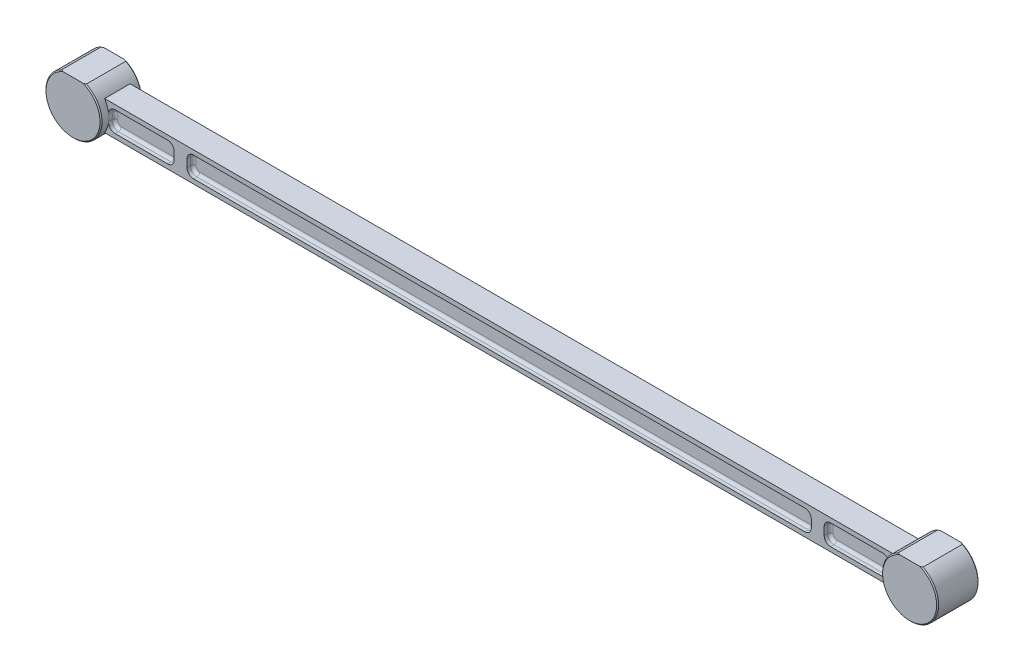
SolidWorks part; units mm, degrees
ref_plane "Front" through (0, 0, 0) normal (0, 0, 1) x (1, 0, 0)
ref_plane "Top" through (0, 0, 0) normal (0, 1, 0) x (1, 0, 0)
ref_plane "Right" through (0, 0, 0) normal (1, 0, 0) x (0, 0, -1)
sketch "Sketch1" plane through (203.1107, -2036.7424, 0) normal (0, 0, 1) x (1, 0, 0)
  line L0 (-203.1107, 2036.7424) -> (-203.1107, 2141.9168)
  line L1 (1096.8893, 2036.7424) -> (1096.8893, 2144.8585)
  line L2 (1044.8723, 2013.7424) -> (-166.1885, 2013.7424)
  line L3 (952.8893, 2018.7424) -> (1042.9378, 2018.7424)
  line L4 (1042.3113, 2052.7424) -> (961.8893, 2052.7424)
  line L5 (1042.9378, 2054.7424) -> (961.8893, 2054.7424)
  line L6 (930.8893, 2059.7424) -> (1044.8723, 2059.7424)
  line L7 (-198.1107, 2081.7424) -> (-208.1107, 2081.7424)
  line L8 (951.8893, 2030.7424) -> (946.8893, 2030.7424)
  line L9 (946.8893, 2030.7424) -> (946.8893, 2042.7424)
  line L10 (951.8893, 2042.7424) -> (951.8893, 2030.7424)
  line L11 (961.8893, 2052.7424) -> (961.8893, 2054.7424)
  line L12 (955.8893, 2050.7424) -> (952.8893, 2054.7424)
  line L13 (927.8893, 2022.7424) -> (930.8893, 2018.7424)
  line L14 (936.8893, 2042.7424) -> (931.8893, 2042.7424)
  line L15 (952.8893, 2054.7424) -> (930.8893, 2054.7424)
  line L16 (961.8893, 2054.7424) -> (952.8893, 2054.7424)
  line L17 (951.8893, 2042.7424) -> (946.8893, 2042.7424)
  line L18 (955.8893, 2022.7424) -> (952.8893, 2018.7424)
  line L19 (936.8893, 2042.7424) -> (936.8893, 2030.7424)
  line L20 (931.8893, 2030.7424) -> (931.8893, 2042.7424)
  line L21 (921.8893, 2057.7424) -> (921.8893, 2052.7424)
  line L22 (921.8893, 2020.7424) -> (921.8893, 2018.7424)
  line L23 (936.8893, 2030.7424) -> (931.8893, 2030.7424)
  line L24 (930.8893, 2054.7424) -> (930.8893, 2059.7424)
  line L25 (921.8893, 2057.7424) -> (921.8893, 2059.7424)
  line L26 (921.8893, 2059.7424) -> (930.8893, 2059.7424)
  line L27 (930.8893, 2018.7424) -> (952.8893, 2018.7424)
  line L28 (921.8893, 2018.7424) -> (930.8893, 2018.7424)
  line L29 (-183.8428, 2075.7424) -> (-222.3785, 2075.7424)
  line L30 (-158.9482, 2018.7424) -> (-149.9482, 2018.7424)
  line L31 (-163.5096, 2018.7424) -> (-158.9482, 2018.7424)
  line L32 (-158.9482, 2054.7424) -> (-158.9482, 2059.7424)
  line L33 (-28.1107, 2057.7424) -> (-28.1107, 2052.7424)
  line L34 (-68.1107, 2018.7424) -> (-68.1107, 2020.7424)
  line L35 (-53.1107, 2030.7424) -> (-58.1107, 2030.7424)
  line L36 (-37.1107, 2054.7424) -> (-59.1107, 2054.7424)
  line L37 (-43.1107, 2030.7424) -> (-43.1107, 2042.7424)
  line L38 (-28.1107, 2057.7424) -> (-28.1107, 2059.7424)
  line L39 (-37.1107, 2059.7424) -> (-28.1107, 2059.7424)
  line L40 (-37.1107, 2054.7424) -> (-37.1107, 2059.7424)
  line L41 (-59.1107, 2054.7424) -> (-59.1107, 2059.7424)
  line L42 (-158.9482, 2054.7424) -> (-163.5096, 2054.7424)
  line L43 (-166.1885, 2059.7424) -> (-158.9482, 2059.7424)
  line L44 (-149.9482, 2057.7424) -> (-68.1107, 2057.7424)
  line L45 (-53.1107, 2042.7424) -> (-53.1107, 2030.7424)
  line L46 (-58.1107, 2030.7424) -> (-58.1107, 2042.7424)
  line L47 (-68.1107, 2052.7424) -> (-149.9482, 2052.7424)
  line L48 (-155.9482, 2022.7424) -> (-158.9482, 2018.7424)
  line L49 (-43.1107, 2042.7424) -> (-38.1107, 2042.7424)
  line L50 (-38.1107, 2030.7424) -> (-43.1107, 2030.7424)
  line L51 (-34.1107, 2022.7424) -> (-37.1107, 2018.7424)
  line L52 (-149.9482, 2018.7424) -> (-149.9482, 2020.7424)
  line L53 (-28.1107, 2020.7424) -> (-28.1107, 2018.7424)
  line L54 (-38.1107, 2042.7424) -> (-38.1107, 2030.7424)
  line L55 (-37.1107, 2018.7424) -> (-28.1107, 2018.7424)
  line L56 (-68.1107, 2057.7424) -> (-68.1107, 2059.7424)
  line L57 (-149.9482, 2057.7424) -> (-149.9482, 2059.7424)
  line L58 (-59.1107, 2059.7424) -> (-37.1107, 2059.7424)
  line L59 (-68.1107, 2059.7424) -> (-59.1107, 2059.7424)
  line L60 (-149.9482, 2059.7424) -> (-68.1107, 2059.7424)
  line L61 (-158.9482, 2059.7424) -> (-149.9482, 2059.7424)
  line L62 (-59.1107, 2018.7424) -> (-37.1107, 2018.7424)
  line L63 (-68.1107, 2018.7424) -> (-59.1107, 2018.7424)
  line L64 (-149.9482, 2018.7424) -> (-68.1107, 2018.7424)
  line L65 (-59.1107, 2018.7424) -> (-62.1107, 2022.7424)
  line L66 (-53.1107, 2042.7424) -> (-58.1107, 2042.7424)
  line L67 (-149.9482, 2020.7424) -> (-68.1107, 2020.7424)
  line L68 (-68.1107, 2057.7424) -> (-68.1107, 2052.7424)
  line L69 (-149.9482, 2057.7424) -> (-149.9482, 2052.7424)
  line L70 (-194.3357, 2074.7424) -> (-185.2221, 2074.7424)
  line L71 (-220.9992, 2074.7424) -> (-211.8857, 2074.7424)
  line L72 (-211.8857, 2074.7424) -> (-194.3357, 2074.7424)
  line L73 (-28.1107, 2057.7424) -> (921.8893, 2057.7424)
  line L74 (-28.1107, 2020.7424) -> (921.8893, 2020.7424)
  line L75 (921.8893, 2052.7424) -> (-28.1107, 2052.7424)
  line L76 (-28.1107, 2059.7424) -> (921.8893, 2059.7424)
  line L77 (-28.1107, 2018.7424) -> (921.8893, 2018.7424)
  line L78 (-208.1107, 2081.7424) -> (-208.1107, 2075.7424)
  line L79 (-198.1107, 2075.7424) -> (-198.1107, 2081.7424)
  arc A0 (-211.8857, 2074.7424) -> (-227.0379, 2005.9448) centre (-203.1107, 2036.7424) ccw
  circle A1 centre (1096.8893, 2036.7424) radius 56.875
  arc A2 (946.8893, 2030.7424) -> (952.8893, 2018.7424) centre (961.8893, 2030.7424) ccw
  arc A3 (952.8893, 2054.7424) -> (946.8893, 2042.7424) centre (961.8893, 2042.7424) ccw
  arc A4 (961.8893, 2052.7424) -> (955.8893, 2050.7424) centre (961.8893, 2042.7424) ccw
  arc A5 (955.8893, 2022.7424) -> (960.8407, 2020.7975) centre (961.8893, 2030.7424) ccw
  arc A6 (955.8893, 2050.7424) -> (951.8893, 2042.7424) centre (961.8893, 2042.7424) ccw
  arc A7 (951.8893, 2030.7424) -> (955.8893, 2022.7424) centre (961.8893, 2030.7424) ccw
  arc A8 (930.8893, 2018.7424) -> (936.8893, 2030.7424) centre (921.8893, 2030.7424) ccw
  arc A9 (936.8893, 2042.7424) -> (930.8893, 2054.7424) centre (921.8893, 2042.7424) ccw
  arc A10 (930.8893, 2054.7424) -> (921.8893, 2057.7424) centre (921.8893, 2042.7424) ccw
  arc A11 (927.8893, 2022.7424) -> (931.8893, 2030.7424) centre (921.8893, 2030.7424) ccw
  arc A12 (921.8893, 2020.7424) -> (927.8893, 2022.7424) centre (921.8893, 2030.7424) ccw
  arc A13 (931.8893, 2042.7424) -> (921.8893, 2052.7424) centre (921.8893, 2042.7424) ccw
  circle A14 centre (1096.8893, 2036.7424) radius 22.5
  circle A15 centre (1096.8893, 2036.7424) radius 27.5
  circle A16 centre (1096.8893, 2036.7424) radius 17.5
  circle A17 centre (1096.8893, 2036.7424) radius 16.5
  circle A18 centre (1132.8893, 2036.7424) radius 4
  circle A19 centre (1132.8893, 2036.7424) radius 3.235
  circle A20 centre (1122.3452, 2062.1982) radius 4
  circle A21 centre (1122.3452, 2062.1982) radius 3.235
  circle A22 centre (1096.8893, 2072.7424) radius 4
  circle A23 centre (1096.8893, 2072.7424) radius 3.235
  circle A24 centre (1071.4335, 2062.1982) radius 4
  circle A25 centre (1071.4335, 2062.1982) radius 3.235
  circle A26 centre (1060.8893, 2036.7424) radius 4
  circle A27 centre (1060.8893, 2036.7424) radius 3.235
  circle A28 centre (1071.4335, 2011.2865) radius 4
  circle A29 centre (1071.4335, 2011.2865) radius 3.235
  circle A30 centre (1096.8893, 2000.7424) radius 4
  circle A31 centre (1096.8893, 2000.7424) radius 3.235
  circle A32 centre (1122.3452, 2011.2865) radius 4
  circle A33 centre (1122.3452, 2011.2865) radius 3.235
  arc A34 (-222.3785, 2075.7424) -> (-236.3766, 2008.7133) centre (-203.1107, 2036.7424) ccw
  arc A35 (-188.7118, 1995.6946) -> (-183.8428, 2075.7424) centre (-203.1107, 2036.7424) ccw
  arc A36 (-28.1107, 2057.7424) -> (-37.1107, 2054.7424) centre (-28.1107, 2042.7424) ccw
  arc A37 (-37.1107, 2054.7424) -> (-43.1107, 2042.7424) centre (-28.1107, 2042.7424) ccw
  arc A38 (-149.9482, 2057.7424) -> (-158.9482, 2054.7424) centre (-149.9482, 2042.7424) ccw
  arc A39 (-158.9482, 2054.7424) -> (-162.169, 2051.4402) centre (-149.9482, 2042.7424) ccw
  arc A40 (-59.1107, 2018.7424) -> (-53.1107, 2030.7424) centre (-68.1107, 2030.7424) ccw
  arc A41 (-68.1107, 2020.7424) -> (-62.1107, 2022.7424) centre (-68.1107, 2030.7424) ccw
  arc A42 (-53.1107, 2042.7424) -> (-59.1107, 2054.7424) centre (-68.1107, 2042.7424) ccw
  arc A43 (-59.1107, 2054.7424) -> (-68.1107, 2057.7424) centre (-68.1107, 2042.7424) ccw
  arc A44 (-155.9482, 2022.7424) -> (-149.9482, 2020.7424) centre (-149.9482, 2030.7424) ccw
  arc A45 (-162.169, 2022.0445) -> (-158.9482, 2018.7424) centre (-149.9482, 2030.7424) ccw
  arc A46 (-159.8851, 2031.8639) -> (-155.9482, 2022.7424) centre (-149.9482, 2030.7424) ccw
  arc A47 (-62.1107, 2022.7424) -> (-58.1107, 2030.7424) centre (-68.1107, 2030.7424) ccw
  arc A48 (-58.1107, 2042.7424) -> (-68.1107, 2052.7424) centre (-68.1107, 2042.7424) ccw
  arc A49 (-149.9482, 2052.7424) -> (-159.8851, 2041.6209) centre (-149.9482, 2042.7424) ccw
  arc A50 (-43.1107, 2030.7424) -> (-37.1107, 2018.7424) centre (-28.1107, 2030.7424) ccw
  arc A51 (-34.1107, 2022.7424) -> (-28.1107, 2020.7424) centre (-28.1107, 2030.7424) ccw
  arc A52 (-38.1107, 2030.7424) -> (-34.1107, 2022.7424) centre (-28.1107, 2030.7424) ccw
  arc A53 (-28.1107, 2052.7424) -> (-38.1107, 2042.7424) centre (-28.1107, 2042.7424) ccw
  arc A54 (-220.9992, 2074.7424) -> (-233.559, 2007.8132) centre (-203.1107, 2036.7424) ccw
  arc A55 (-190.248, 1996.7605) -> (-185.2221, 2074.7424) centre (-203.1107, 2036.7424) ccw
  arc A56 (-197.6959, 1998.1201) -> (-194.3357, 2074.7424) centre (-203.1107, 2036.7424) ccw
  circle A57 centre (1096.8893, 2036.7424) radius 52
sketch "Sketch2" plane through (203.1107, 0, 2326.2596) normal (0, 1, 0) x (1, 0, 0)
  line L0 (-203.1107, 2177.2171) -> (-203.1107, 2506.6867)
  line L1 (1096.8893, 2174.2754) -> (1096.8893, 2480.2115)
  line L2 (-223.1107, 2362.7596) -> (-223.1107, 2358.2596)
  line L3 (-183.1107, 2358.2596) -> (-183.1107, 2362.7596)
  line L4 (1088.1143, 2365.2596) -> (1079.0008, 2362.2596)
  line L5 (1114.7779, 2362.2596) -> (1105.6643, 2365.2596)
  line L6 (1138.8893, 2362.2596) -> (1135.8893, 2365.2596)
  line L7 (1057.8893, 2365.2596) -> (1054.8893, 2362.2596)
  line L8 (-28.1107, 2306.2596) -> (921.8893, 2306.2596)
  line L9 (1059.9671, 2341.2596) -> (-59.1107, 2341.2596)
  line L10 (-28.1107, 2346.2596) -> (921.8893, 2346.2596)
  line L11 (-28.1107, 2310.2596) -> (921.8893, 2310.2596)
  line L12 (-159.6107, 2294.2596) -> (-159.6107, 2306.2596)
  line L13 (-246.6107, 2358.2596) -> (-246.6107, 2294.2596)
  line L14 (-183.8428, 2358.2596) -> (-222.3785, 2358.2596)
  line L15 (-183.8428, 2358.2596) -> (-183.8428, 2294.2596)
  line L16 (-183.8428, 2294.2596) -> (-222.3785, 2294.2596)
  line L17 (-222.3785, 2294.2596) -> (-222.3785, 2358.2596)
  line L18 (-246.6107, 2358.2596) -> (-222.3785, 2358.2596)
  line L19 (-183.8428, 2358.2596) -> (-159.6107, 2358.2596)
  line L20 (-246.6107, 2294.2596) -> (-222.3785, 2294.2596)
  line L21 (-183.8428, 2294.2596) -> (-159.6107, 2294.2596)
  line L22 (-166.1885, 2341.2596) -> (-166.1865, 2341.2994)
  line L23 (-166.1865, 2341.2994) -> (-166.1844, 2341.3393)
  line L24 (-166.1844, 2341.3393) -> (-166.1824, 2341.3792)
  line L25 (-166.1824, 2341.3792) -> (-166.1803, 2341.4191)
  line L26 (-166.1803, 2341.4191) -> (-166.1781, 2341.4589)
  line L27 (-166.1781, 2341.4589) -> (-166.176, 2341.4988)
  line L28 (-166.176, 2341.4988) -> (-166.1737, 2341.5386)
  line L29 (-166.1737, 2341.5386) -> (-166.1715, 2341.5785)
  line L30 (-166.1715, 2341.5785) -> (-166.1691, 2341.6183)
  line L31 (-166.1691, 2341.6183) -> (-166.1667, 2341.6582)
  line L32 (-166.1667, 2341.6582) -> (-166.1644, 2341.6958)
  line L33 (-166.1644, 2341.6958) -> (-166.162, 2341.7334)
  line L34 (-166.162, 2341.7334) -> (-166.1595, 2341.7709)
  line L35 (-166.1595, 2341.7709) -> (-166.157, 2341.8085)
  line L36 (-166.157, 2341.8085) -> (-166.1543, 2341.8461)
  line L37 (-166.1543, 2341.8461) -> (-166.1516, 2341.8836)
  line L38 (-166.1516, 2341.8836) -> (-166.1488, 2341.9212)
  line L39 (-166.1488, 2341.9212) -> (-166.1459, 2341.9587)
  line L40 (-166.1459, 2341.9587) -> (-166.1428, 2341.9963)
  line L41 (-166.1428, 2341.9963) -> (-166.1397, 2342.0338)
  line L42 (-166.1397, 2342.0338) -> (-166.1365, 2342.0697)
  line L43 (-166.1365, 2342.0697) -> (-166.1332, 2342.1057)
  line L44 (-166.1332, 2342.1057) -> (-166.1299, 2342.1416)
  line L45 (-166.1299, 2342.1416) -> (-166.1263, 2342.1776)
  line L46 (-166.1263, 2342.1776) -> (-166.1227, 2342.2135)
  line L47 (-166.1227, 2342.2135) -> (-166.1189, 2342.2494)
  line L48 (-166.1189, 2342.2494) -> (-166.115, 2342.2853)
  line L49 (-166.115, 2342.2853) -> (-166.1109, 2342.3212)
  line L50 (-166.1109, 2342.3212) -> (-166.1066, 2342.357)
  line L51 (-166.1066, 2342.357) -> (-166.1022, 2342.3929)
  line L52 (-166.1022, 2342.3929) -> (-166.0977, 2342.4279)
  line L53 (-166.0977, 2342.4279) -> (-166.0931, 2342.4629)
  line L54 (-166.0931, 2342.4629) -> (-166.0883, 2342.4979)
  line L55 (-166.0883, 2342.4979) -> (-166.0833, 2342.5329)
  line L56 (-166.0833, 2342.5329) -> (-166.0781, 2342.5678)
  line L57 (-166.0781, 2342.5678) -> (-166.0727, 2342.6027)
  line L58 (-166.0727, 2342.6027) -> (-166.0672, 2342.6376)
  line L59 (-166.0672, 2342.6376) -> (-166.0614, 2342.6724)
  line L60 (-166.0614, 2342.6724) -> (-166.0555, 2342.7072)
  line L61 (-166.0555, 2342.7072) -> (-166.0494, 2342.742)
  line L62 (-166.0494, 2342.742) -> (-166.0431, 2342.7765)
  line L63 (-166.0431, 2342.7765) -> (-166.0366, 2342.8109)
  line L64 (-166.0366, 2342.8109) -> (-166.0299, 2342.8453)
  line L65 (-166.0299, 2342.8453) -> (-166.023, 2342.8797)
  line L66 (-166.023, 2342.8797) -> (-166.0159, 2342.914)
  line L67 (-166.0159, 2342.914) -> (-166.0087, 2342.9483)
  line L68 (-166.0087, 2342.9483) -> (-166.0012, 2342.9826)
  line L69 (-166.0012, 2342.9826) -> (-165.9936, 2343.0168)
  line L70 (-165.9936, 2343.0168) -> (-165.9857, 2343.0509)
  line L71 (-165.9857, 2343.0509) -> (-165.9777, 2343.0851)
  line L72 (-165.9777, 2343.0851) -> (-165.9696, 2343.1188)
  line L73 (-165.9696, 2343.1188) -> (-165.9613, 2343.1525)
  line L74 (-165.9613, 2343.1525) -> (-165.9528, 2343.1862)
  line L75 (-165.9528, 2343.1862) -> (-165.9442, 2343.2198)
  line L76 (-165.9442, 2343.2198) -> (-165.9354, 2343.2534)
  line L77 (-165.9354, 2343.2534) -> (-165.9264, 2343.2869)
  line L78 (-165.9264, 2343.2869) -> (-165.9172, 2343.3204)
  line L79 (-165.9172, 2343.3204) -> (-165.9079, 2343.3539)
  line L80 (-165.9079, 2343.3539) -> (-165.8984, 2343.3872)
  line L81 (-165.8984, 2343.3872) -> (-165.8887, 2343.4206)
  line L82 (-165.8887, 2343.4206) -> (-165.8791, 2343.4532)
  line L83 (-165.8791, 2343.4532) -> (-165.8693, 2343.4858)
  line L84 (-165.8693, 2343.4858) -> (-165.8594, 2343.5183)
  line L85 (-165.8594, 2343.5183) -> (-165.8493, 2343.5507)
  line L86 (-165.8493, 2343.5507) -> (-165.839, 2343.5832)
  line L87 (-165.839, 2343.5832) -> (-165.8286, 2343.6155)
  line L88 (-165.8286, 2343.6155) -> (-165.8181, 2343.6478)
  line L89 (-165.8181, 2343.6478) -> (-165.8073, 2343.6801)
  line L90 (-165.8073, 2343.6801) -> (-165.7965, 2343.7123)
  line L91 (-165.7965, 2343.7123) -> (-165.7854, 2343.7445)
  line L92 (-165.7854, 2343.7445) -> (-165.7746, 2343.7755)
  line L93 (-165.7746, 2343.7755) -> (-165.7636, 2343.8065)
  line L94 (-165.7636, 2343.8065) -> (-165.7525, 2343.8375)
  line L95 (-165.7525, 2343.8375) -> (-165.7413, 2343.8684)
  line L96 (-165.7413, 2343.8684) -> (-165.7299, 2343.8992)
  line L97 (-165.7299, 2343.8992) -> (-165.7183, 2343.93)
  line L98 (-165.7183, 2343.93) -> (-165.7066, 2343.9607)
  line L99 (-165.7066, 2343.9607) -> (-165.6948, 2343.9914)
  line L100 (-165.6948, 2343.9914) -> (-165.6828, 2344.022)
  line L101 (-165.6828, 2344.022) -> (-165.6707, 2344.0526)
  line L102 (-165.6707, 2344.0526) -> (-165.6582, 2344.0837)
  line L103 (-165.6582, 2344.0837) -> (-165.6455, 2344.1147)
  line L104 (-165.6455, 2344.1147) -> (-165.6327, 2344.1456)
  line L105 (-165.6327, 2344.1456) -> (-165.6197, 2344.1765)
  line L106 (-165.6197, 2344.1765) -> (-165.6066, 2344.2074)
  line L107 (-165.6066, 2344.2074) -> (-165.5933, 2344.2381)
  line L108 (-165.5933, 2344.2381) -> (-165.5798, 2344.2688)
  line L109 (-165.5798, 2344.2688) -> (-165.5662, 2344.2994)
  line L110 (-165.5662, 2344.2994) -> (-165.5524, 2344.33)
  line L111 (-165.5524, 2344.33) -> (-165.5385, 2344.3604)
  line L112 (-165.5385, 2344.3604) -> (-165.5251, 2344.3893)
  line L113 (-165.5251, 2344.3893) -> (-165.5115, 2344.4182)
  line L114 (-165.5115, 2344.4182) -> (-165.4978, 2344.447)
  line L115 (-165.4978, 2344.447) -> (-165.4839, 2344.4756)
  line L116 (-165.4839, 2344.4756) -> (-165.4699, 2344.5043)
  line L117 (-165.4699, 2344.5043) -> (-165.4557, 2344.5328)
  line L118 (-165.4557, 2344.5328) -> (-165.4413, 2344.5613)
  line L119 (-165.4413, 2344.5613) -> (-165.4268, 2344.5897)
  line L120 (-165.4268, 2344.5897) -> (-165.4122, 2344.618)
  line L121 (-165.4122, 2344.618) -> (-165.3973, 2344.6462)
  line L122 (-165.3973, 2344.6462) -> (-165.3831, 2344.673)
  line L123 (-165.3831, 2344.673) -> (-165.3686, 2344.6997)
  line L124 (-165.3686, 2344.6997) -> (-165.3541, 2344.7263)
  line L125 (-165.3541, 2344.7263) -> (-165.3394, 2344.7529)
  line L126 (-165.3394, 2344.7529) -> (-165.3245, 2344.7794)
  line L127 (-165.3245, 2344.7794) -> (-165.3095, 2344.8058)
  line L128 (-165.3095, 2344.8058) -> (-165.2943, 2344.8321)
  line L129 (-165.2943, 2344.8321) -> (-165.279, 2344.8583)
  line L130 (-165.279, 2344.8583) -> (-165.2635, 2344.8844)
  line L131 (-165.2635, 2344.8844) -> (-165.2479, 2344.9104)
  line L132 (-165.2479, 2344.9104) -> (-165.2328, 2344.9352)
  line L133 (-165.2328, 2344.9352) -> (-165.2176, 2344.9599)
  line L134 (-165.2176, 2344.9599) -> (-165.2022, 2344.9844)
  line L135 (-165.2022, 2344.9844) -> (-165.1868, 2345.0089)
  line L136 (-165.1868, 2345.0089) -> (-165.1711, 2345.0333)
  line L137 (-165.1711, 2345.0333) -> (-165.1553, 2345.0576)
  line L138 (-165.1553, 2345.0576) -> (-165.1394, 2345.0818)
  line L139 (-165.1394, 2345.0818) -> (-165.1233, 2345.1059)
  line L140 (-165.1233, 2345.1059) -> (-165.1071, 2345.1299)
  line L141 (-165.1071, 2345.1299) -> (-165.0907, 2345.1538)
  line L142 (-165.0907, 2345.1538) -> (-165.0728, 2345.1797)
  line L143 (-165.0728, 2345.1797) -> (-165.0547, 2345.2054)
  line L144 (-165.0547, 2345.2054) -> (-165.0364, 2345.231)
  line L145 (-165.0364, 2345.231) -> (-165.0179, 2345.2564)
  line L146 (-165.0179, 2345.2564) -> (-164.9992, 2345.2818)
  line L147 (-164.9992, 2345.2818) -> (-164.9804, 2345.307)
  line L148 (-164.9804, 2345.307) -> (-164.9613, 2345.332)
  line L149 (-164.9613, 2345.332) -> (-164.9421, 2345.3569)
  line L150 (-164.9421, 2345.3569) -> (-164.9227, 2345.3817)
  line L151 (-164.9227, 2345.3817) -> (-164.9031, 2345.4063)
  line L152 (-164.9031, 2345.4063) -> (-164.8846, 2345.4292)
  line L153 (-164.8846, 2345.4292) -> (-164.8659, 2345.4519)
  line L154 (-164.8659, 2345.4519) -> (-164.847, 2345.4746)
  line L155 (-164.847, 2345.4746) -> (-164.828, 2345.497)
  line L156 (-164.828, 2345.497) -> (-164.8088, 2345.5194)
  line L157 (-164.8088, 2345.5194) -> (-164.7893, 2345.5415)
  line L158 (-164.7893, 2345.5415) -> (-164.7697, 2345.5635)
  line L159 (-164.7697, 2345.5635) -> (-164.75, 2345.5853)
  line L160 (-164.75, 2345.5853) -> (-164.73, 2345.607)
  line L161 (-164.73, 2345.607) -> (-164.7098, 2345.6285)
  line L162 (-164.7098, 2345.6285) -> (-164.6911, 2345.6481)
  line L163 (-164.6911, 2345.6481) -> (-164.6722, 2345.6675)
  line L164 (-164.6722, 2345.6675) -> (-164.6531, 2345.6868)
  line L165 (-164.6531, 2345.6868) -> (-164.6338, 2345.7059)
  line L166 (-164.6338, 2345.7059) -> (-164.6144, 2345.7249)
  line L167 (-164.6144, 2345.7249) -> (-164.5948, 2345.7436)
  line L168 (-164.5948, 2345.7436) -> (-164.575, 2345.7622)
  line L169 (-164.575, 2345.7622) -> (-164.555, 2345.7805)
  line L170 (-164.555, 2345.7805) -> (-164.5348, 2345.7986)
  line L171 (-164.5348, 2345.7986) -> (-164.5144, 2345.8165)
  line L172 (-164.5144, 2345.8165) -> (-164.4958, 2345.8325)
  line L173 (-164.4958, 2345.8325) -> (-164.477, 2345.8483)
  line L174 (-164.477, 2345.8483) -> (-164.458, 2345.8639)
  line L175 (-164.458, 2345.8639) -> (-164.4389, 2345.8793)
  line L176 (-164.4389, 2345.8793) -> (-164.4196, 2345.8945)
  line L177 (-164.4196, 2345.8945) -> (-164.4001, 2345.9095)
  line L178 (-164.4001, 2345.9095) -> (-164.3804, 2345.9241)
  line L179 (-164.3804, 2345.9241) -> (-164.3605, 2345.9386)
  line L180 (-164.3605, 2345.9386) -> (-164.3405, 2345.9527)
  line L181 (-164.3405, 2345.9527) -> (-164.3203, 2345.9666)
  line L182 (-164.3203, 2345.9666) -> (-164.3013, 2345.9792)
  line L183 (-164.3013, 2345.9792) -> (-164.2822, 2345.9916)
  line L184 (-164.2822, 2345.9916) -> (-164.2628, 2346.0037)
  line L185 (-164.2628, 2346.0037) -> (-164.2434, 2346.0155)
  line L186 (-164.2434, 2346.0155) -> (-164.2237, 2346.027)
  line L187 (-164.2237, 2346.027) -> (-164.2039, 2346.0383)
  line L188 (-164.2039, 2346.0383) -> (-164.1839, 2346.0492)
  line L189 (-164.1839, 2346.0492) -> (-164.1638, 2346.0599)
  line L190 (-164.1638, 2346.0599) -> (-164.1435, 2346.0703)
  line L191 (-164.1435, 2346.0703) -> (-164.1231, 2346.0803)
  line L192 (-164.1231, 2346.0803) -> (-164.1039, 2346.0894)
  line L193 (-164.1039, 2346.0894) -> (-164.0845, 2346.0983)
  line L194 (-164.0845, 2346.0983) -> (-164.065, 2346.1069)
  line L195 (-164.065, 2346.1069) -> (-164.0454, 2346.1152)
  line L196 (-164.0454, 2346.1152) -> (-164.0257, 2346.1233)
  line L197 (-164.0257, 2346.1233) -> (-164.0059, 2346.1312)
  line L198 (-164.0059, 2346.1312) -> (-163.986, 2346.1387)
  line L199 (-163.986, 2346.1387) -> (-163.966, 2346.1461)
  line L200 (-163.966, 2346.1461) -> (-163.9459, 2346.1531)
  line L201 (-163.9459, 2346.1531) -> (-163.9258, 2346.16)
  line L202 (-163.9258, 2346.16) -> (-163.9058, 2346.1665)
  line L203 (-163.9058, 2346.1665) -> (-163.8857, 2346.1728)
  line L204 (-163.8857, 2346.1728) -> (-163.8655, 2346.1789)
  line L205 (-163.8655, 2346.1789) -> (-163.8453, 2346.1847)
  line L206 (-163.8453, 2346.1847) -> (-163.8251, 2346.1904)
  line L207 (-163.8251, 2346.1904) -> (-163.8047, 2346.1959)
  line L208 (-163.8047, 2346.1959) -> (-163.7844, 2346.2012)
  line L209 (-163.7844, 2346.2012) -> (-163.764, 2346.2064)
  line L210 (-163.764, 2346.2064) -> (-163.7435, 2346.2114)
  line L211 (-163.7435, 2346.2114) -> (-163.723, 2346.2162)
  line L212 (-163.723, 2346.2162) -> (-163.7018, 2346.221)
  line L213 (-163.7018, 2346.221) -> (-163.6805, 2346.2257)
  line L214 (-163.6805, 2346.2257) -> (-163.6592, 2346.2303)
  line L215 (-163.6592, 2346.2303) -> (-163.6379, 2346.2348)
  line L216 (-163.6379, 2346.2348) -> (-163.6165, 2346.2391)
  line L217 (-163.6165, 2346.2391) -> (-163.5952, 2346.2434)
  line L218 (-163.5952, 2346.2434) -> (-163.5738, 2346.2475)
  line L219 (-163.5738, 2346.2475) -> (-163.5524, 2346.2516)
  line L220 (-163.5524, 2346.2516) -> (-163.531, 2346.2556)
  line L221 (-163.531, 2346.2556) -> (-163.5096, 2346.2596)
  line L222 (-158.9482, 2306.2596) -> (-158.9482, 2311.2596)
  line L223 (-163.5096, 2306.2596) -> (-163.5328, 2306.2642)
  line L224 (-163.5328, 2306.2642) -> (-163.556, 2306.2689)
  line L225 (-163.556, 2306.2689) -> (-163.5792, 2306.2736)
  line L226 (-163.5792, 2306.2736) -> (-163.6024, 2306.2785)
  line L227 (-163.6024, 2306.2785) -> (-163.6256, 2306.2834)
  line L228 (-163.6256, 2306.2834) -> (-163.6487, 2306.2885)
  line L229 (-163.6487, 2306.2885) -> (-163.6718, 2306.2937)
  line L230 (-163.6718, 2306.2937) -> (-163.6949, 2306.2991)
  line L231 (-163.6949, 2306.2991) -> (-163.718, 2306.3046)
  line L232 (-163.718, 2306.3046) -> (-163.741, 2306.3102)
  line L233 (-163.741, 2306.3102) -> (-163.7632, 2306.3159)
  line L234 (-163.7632, 2306.3159) -> (-163.7854, 2306.3217)
  line L235 (-163.7854, 2306.3217) -> (-163.8076, 2306.3277)
  line L236 (-163.8076, 2306.3277) -> (-163.8297, 2306.334)
  line L237 (-163.8297, 2306.334) -> (-163.8517, 2306.3404)
  line L238 (-163.8517, 2306.3404) -> (-163.8737, 2306.347)
  line L239 (-163.8737, 2306.347) -> (-163.8956, 2306.3539)
  line L240 (-163.8956, 2306.3539) -> (-163.9174, 2306.361)
  line L241 (-163.9174, 2306.361) -> (-163.9391, 2306.3684)
  line L242 (-163.9391, 2306.3684) -> (-163.9608, 2306.376)
  line L243 (-163.9608, 2306.376) -> (-163.9827, 2306.384)
  line L244 (-163.9827, 2306.384) -> (-164.0045, 2306.3923)
  line L245 (-164.0045, 2306.3923) -> (-164.0262, 2306.4009)
  line L246 (-164.0262, 2306.4009) -> (-164.0477, 2306.4098)
  line L247 (-164.0477, 2306.4098) -> (-164.0692, 2306.4189)
  line L248 (-164.0692, 2306.4189) -> (-164.0905, 2306.4284)
  line L249 (-164.0905, 2306.4284) -> (-164.1117, 2306.4381)
  line L250 (-164.1117, 2306.4381) -> (-164.1328, 2306.4482)
  line L251 (-164.1328, 2306.4482) -> (-164.1537, 2306.4585)
  line L252 (-164.1537, 2306.4585) -> (-164.1744, 2306.4691)
  line L253 (-164.1744, 2306.4691) -> (-164.1966, 2306.4809)
  line L254 (-164.1966, 2306.4809) -> (-164.2186, 2306.4931)
  line L255 (-164.2186, 2306.4931) -> (-164.2404, 2306.5055)
  line L256 (-164.2404, 2306.5055) -> (-164.262, 2306.5184)
  line L257 (-164.262, 2306.5184) -> (-164.2834, 2306.5315)
  line L258 (-164.2834, 2306.5315) -> (-164.3046, 2306.545)
  line L259 (-164.3046, 2306.545) -> (-164.3256, 2306.5587)
  line L260 (-164.3256, 2306.5587) -> (-164.3464, 2306.5728)
  line L261 (-164.3464, 2306.5728) -> (-164.367, 2306.5872)
  line L262 (-164.367, 2306.5872) -> (-164.3874, 2306.6018)
  line L263 (-164.3874, 2306.6018) -> (-164.4101, 2306.6187)
  line L264 (-164.4101, 2306.6187) -> (-164.4325, 2306.6358)
  line L265 (-164.4325, 2306.6358) -> (-164.4547, 2306.6533)
  line L266 (-164.4547, 2306.6533) -> (-164.4767, 2306.6711)
  line L267 (-164.4767, 2306.6711) -> (-164.4984, 2306.6892)
  line L268 (-164.4984, 2306.6892) -> (-164.5199, 2306.7076)
  line L269 (-164.5199, 2306.7076) -> (-164.5411, 2306.7262)
  line L270 (-164.5411, 2306.7262) -> (-164.5622, 2306.7451)
  line L271 (-164.5622, 2306.7451) -> (-164.583, 2306.7642)
  line L272 (-164.583, 2306.7642) -> (-164.6036, 2306.7836)
  line L273 (-164.6036, 2306.7836) -> (-164.6263, 2306.8054)
  line L274 (-164.6263, 2306.8054) -> (-164.6488, 2306.8275)
  line L275 (-164.6488, 2306.8275) -> (-164.671, 2306.8498)
  line L276 (-164.671, 2306.8498) -> (-164.693, 2306.8723)
  line L277 (-164.693, 2306.8723) -> (-164.7148, 2306.8951)
  line L278 (-164.7148, 2306.8951) -> (-164.7363, 2306.9182)
  line L279 (-164.7363, 2306.9182) -> (-164.7576, 2306.9414)
  line L280 (-164.7576, 2306.9414) -> (-164.7787, 2306.9648)
  line L281 (-164.7787, 2306.9648) -> (-164.7995, 2306.9884)
  line L282 (-164.7995, 2306.9884) -> (-164.8202, 2307.0122)
  line L283 (-164.8202, 2307.0122) -> (-164.8425, 2307.0385)
  line L284 (-164.8425, 2307.0385) -> (-164.8646, 2307.0649)
  line L285 (-164.8646, 2307.0649) -> (-164.8864, 2307.0915)
  line L286 (-164.8864, 2307.0915) -> (-164.908, 2307.1184)
  line L287 (-164.908, 2307.1184) -> (-164.9294, 2307.1454)
  line L288 (-164.9294, 2307.1454) -> (-164.9505, 2307.1726)
  line L289 (-164.9505, 2307.1726) -> (-164.9714, 2307.2)
  line L290 (-164.9714, 2307.2) -> (-164.9921, 2307.2275)
  line L291 (-164.9921, 2307.2275) -> (-165.0126, 2307.2552)
  line L292 (-165.0126, 2307.2552) -> (-165.0328, 2307.2831)
  line L293 (-165.0328, 2307.2831) -> (-165.0543, 2307.3131)
  line L294 (-165.0543, 2307.3131) -> (-165.0756, 2307.3434)
  line L295 (-165.0756, 2307.3434) -> (-165.0966, 2307.3738)
  line L296 (-165.0966, 2307.3738) -> (-165.1174, 2307.4044)
  line L297 (-165.1174, 2307.4044) -> (-165.1379, 2307.4352)
  line L298 (-165.1379, 2307.4352) -> (-165.1583, 2307.4661)
  line L299 (-165.1583, 2307.4661) -> (-165.1783, 2307.4971)
  line L300 (-165.1783, 2307.4971) -> (-165.1982, 2307.5283)
  line L301 (-165.1982, 2307.5283) -> (-165.2178, 2307.5597)
  line L302 (-165.2178, 2307.5597) -> (-165.2372, 2307.5911)
  line L303 (-165.2372, 2307.5911) -> (-165.2571, 2307.6239)
  line L304 (-165.2571, 2307.6239) -> (-165.2767, 2307.6568)
  line L305 (-165.2767, 2307.6568) -> (-165.2961, 2307.6899)
  line L306 (-165.2961, 2307.6899) -> (-165.3153, 2307.7231)
  line L307 (-165.3153, 2307.7231) -> (-165.3342, 2307.7564)
  line L308 (-165.3342, 2307.7564) -> (-165.3529, 2307.7899)
  line L309 (-165.3529, 2307.7899) -> (-165.3714, 2307.8235)
  line L310 (-165.3714, 2307.8235) -> (-165.3896, 2307.8572)
  line L311 (-165.3896, 2307.8572) -> (-165.4076, 2307.8911)
  line L312 (-165.4076, 2307.8911) -> (-165.4254, 2307.925)
  line L313 (-165.4254, 2307.925) -> (-165.4439, 2307.961)
  line L314 (-165.4439, 2307.961) -> (-165.4621, 2307.9972)
  line L315 (-165.4621, 2307.9972) -> (-165.4801, 2308.0334)
  line L316 (-165.4801, 2308.0334) -> (-165.4979, 2308.0698)
  line L317 (-165.4979, 2308.0698) -> (-165.5153, 2308.1063)
  line L318 (-165.5153, 2308.1063) -> (-165.5326, 2308.1429)
  line L319 (-165.5326, 2308.1429) -> (-165.5496, 2308.1797)
  line L320 (-165.5496, 2308.1797) -> (-165.5663, 2308.2165)
  line L321 (-165.5663, 2308.2165) -> (-165.5828, 2308.2535)
  line L322 (-165.5828, 2308.2535) -> (-165.599, 2308.2906)
  line L323 (-165.599, 2308.2906) -> (-165.6159, 2308.3298)
  line L324 (-165.6159, 2308.3298) -> (-165.6325, 2308.3692)
  line L325 (-165.6325, 2308.3692) -> (-165.6488, 2308.4088)
  line L326 (-165.6488, 2308.4088) -> (-165.6649, 2308.4484)
  line L327 (-165.6649, 2308.4484) -> (-165.6807, 2308.4881)
  line L328 (-165.6807, 2308.4881) -> (-165.6962, 2308.528)
  line L329 (-165.6962, 2308.528) -> (-165.7115, 2308.5679)
  line L330 (-165.7115, 2308.5679) -> (-165.7264, 2308.6079)
  line L331 (-165.7264, 2308.6079) -> (-165.7412, 2308.6481)
  line L332 (-165.7412, 2308.6481) -> (-165.7556, 2308.6883)
  line L333 (-165.7556, 2308.6883) -> (-165.7706, 2308.7309)
  line L334 (-165.7706, 2308.7309) -> (-165.7854, 2308.7737)
  line L335 (-165.7854, 2308.7737) -> (-165.7998, 2308.8165)
  line L336 (-165.7998, 2308.8165) -> (-165.8139, 2308.8594)
  line L337 (-165.8139, 2308.8594) -> (-165.8278, 2308.9024)
  line L338 (-165.8278, 2308.9024) -> (-165.8414, 2308.9456)
  line L339 (-165.8414, 2308.9456) -> (-165.8547, 2308.9888)
  line L340 (-165.8547, 2308.9888) -> (-165.8677, 2309.032)
  line L341 (-165.8677, 2309.032) -> (-165.8804, 2309.0754)
  line L342 (-165.8804, 2309.0754) -> (-165.8929, 2309.1188)
  line L343 (-165.8929, 2309.1188) -> (-165.9041, 2309.159)
  line L344 (-165.9041, 2309.159) -> (-165.9152, 2309.1992)
  line L345 (-165.9152, 2309.1992) -> (-165.9259, 2309.2394)
  line L346 (-165.9259, 2309.2394) -> (-165.9365, 2309.2797)
  line L347 (-165.9365, 2309.2797) -> (-165.9469, 2309.3201)
  line L348 (-165.9469, 2309.3201) -> (-165.957, 2309.3605)
  line L349 (-165.957, 2309.3605) -> (-165.9669, 2309.401)
  line L350 (-165.9669, 2309.401) -> (-165.9766, 2309.4416)
  line L351 (-165.9766, 2309.4416) -> (-165.986, 2309.4821)
  line L352 (-165.986, 2309.4821) -> (-165.9953, 2309.5228)
  line L353 (-165.9953, 2309.5228) -> (-166.0046, 2309.5646)
  line L354 (-166.0046, 2309.5646) -> (-166.0137, 2309.6065)
  line L355 (-166.0137, 2309.6065) -> (-166.0225, 2309.6484)
  line L356 (-166.0225, 2309.6484) -> (-166.0312, 2309.6903)
  line L357 (-166.0312, 2309.6903) -> (-166.0396, 2309.7324)
  line L358 (-166.0396, 2309.7324) -> (-166.0477, 2309.7744)
  line L359 (-166.0477, 2309.7744) -> (-166.0557, 2309.8165)
  line L360 (-166.0557, 2309.8165) -> (-166.0634, 2309.8587)
  line L361 (-166.0634, 2309.8587) -> (-166.0709, 2309.9008)
  line L362 (-166.0709, 2309.9008) -> (-166.0782, 2309.943)
  line L363 (-166.0782, 2309.943) -> (-166.0854, 2309.9856)
  line L364 (-166.0854, 2309.9856) -> (-166.0922, 2310.0282)
  line L365 (-166.0922, 2310.0282) -> (-166.0989, 2310.0709)
  line L366 (-166.0989, 2310.0709) -> (-166.1053, 2310.1135)
  line L367 (-166.1053, 2310.1135) -> (-166.1115, 2310.1562)
  line L368 (-166.1115, 2310.1562) -> (-166.1175, 2310.199)
  line L369 (-166.1175, 2310.199) -> (-166.1232, 2310.2418)
  line L370 (-166.1232, 2310.2418) -> (-166.1287, 2310.2846)
  line L371 (-166.1287, 2310.2846) -> (-166.134, 2310.3274)
  line L372 (-166.134, 2310.3274) -> (-166.139, 2310.3703)
  line L373 (-166.139, 2310.3703) -> (-166.1437, 2310.4126)
  line L374 (-166.1437, 2310.4126) -> (-166.1482, 2310.455)
  line L375 (-166.1482, 2310.455) -> (-166.1525, 2310.4975)
  line L376 (-166.1525, 2310.4975) -> (-166.1564, 2310.5399)
  line L377 (-166.1564, 2310.5399) -> (-166.1602, 2310.5824)
  line L378 (-166.1602, 2310.5824) -> (-166.1637, 2310.6249)
  line L379 (-166.1637, 2310.6249) -> (-166.1669, 2310.6674)
  line L380 (-166.1669, 2310.6674) -> (-166.1699, 2310.7099)
  line L381 (-166.1699, 2310.7099) -> (-166.1726, 2310.7525)
  line L382 (-166.1726, 2310.7525) -> (-166.175, 2310.7951)
  line L383 (-166.175, 2310.7951) -> (-166.1756, 2310.8062)
  line L384 (-166.1756, 2310.8062) -> (-166.1762, 2310.8173)
  line L385 (-166.1762, 2310.8173) -> (-166.1767, 2310.8284)
  line L386 (-166.1767, 2310.8284) -> (-166.1773, 2310.8395)
  line L387 (-166.1773, 2310.8395) -> (-166.1778, 2310.8506)
  line L388 (-166.1778, 2310.8506) -> (-166.1783, 2310.8617)
  line L389 (-166.1783, 2310.8617) -> (-166.1788, 2310.8728)
  line L390 (-166.1788, 2310.8728) -> (-166.1792, 2310.8839)
  line L391 (-166.1792, 2310.8839) -> (-166.1797, 2310.895)
  line L392 (-166.1797, 2310.895) -> (-166.1801, 2310.9061)
  line L393 (-166.1801, 2310.9061) -> (-166.1806, 2310.9174)
  line L394 (-166.1806, 2310.9174) -> (-166.181, 2310.9287)
  line L395 (-166.181, 2310.9287) -> (-166.1814, 2310.94)
  line L396 (-166.1814, 2310.94) -> (-166.1818, 2310.9512)
  line L397 (-166.1818, 2310.9512) -> (-166.1821, 2310.9625)
  line L398 (-166.1821, 2310.9625) -> (-166.1825, 2310.9738)
  line L399 (-166.1825, 2310.9738) -> (-166.1828, 2310.9851)
  line L400 (-166.1828, 2310.9851) -> (-166.1832, 2310.9964)
  line L401 (-166.1832, 2310.9964) -> (-166.1835, 2311.0076)
  line L402 (-166.1835, 2311.0076) -> (-166.1838, 2311.0189)
  line L403 (-166.1838, 2311.0189) -> (-166.1841, 2311.0306)
  line L404 (-166.1841, 2311.0306) -> (-166.1844, 2311.0423)
  line L405 (-166.1844, 2311.0423) -> (-166.1847, 2311.054)
  line L406 (-166.1847, 2311.054) -> (-166.1849, 2311.0657)
  line L407 (-166.1849, 2311.0657) -> (-166.1852, 2311.0774)
  line L408 (-166.1852, 2311.0774) -> (-166.1855, 2311.0891)
  line L409 (-166.1855, 2311.0891) -> (-166.1857, 2311.1008)
  line L410 (-166.1857, 2311.1008) -> (-166.186, 2311.1125)
  line L411 (-166.186, 2311.1125) -> (-166.1862, 2311.1242)
  line L412 (-166.1862, 2311.1242) -> (-166.1864, 2311.1359)
  line L413 (-166.1864, 2311.1359) -> (-166.1866, 2311.1483)
  line L414 (-166.1866, 2311.1483) -> (-166.1869, 2311.1606)
  line L415 (-166.1869, 2311.1606) -> (-166.1871, 2311.173)
  line L416 (-166.1871, 2311.173) -> (-166.1873, 2311.1854)
  line L417 (-166.1873, 2311.1854) -> (-166.1875, 2311.1977)
  line L418 (-166.1875, 2311.1977) -> (-166.1877, 2311.2101)
  line L419 (-166.1877, 2311.2101) -> (-166.1879, 2311.2225)
  line L420 (-166.1879, 2311.2225) -> (-166.1881, 2311.2348)
  line L421 (-166.1881, 2311.2348) -> (-166.1883, 2311.2472)
  line L422 (-166.1883, 2311.2472) -> (-166.1885, 2311.2596)
  line L423 (-68.1107, 2342.2596) -> (-68.1107, 2346.2596)
  line L424 (-37.1107, 2306.2596) -> (-28.1107, 2306.2596)
  line L425 (-37.1107, 2306.2596) -> (-59.1107, 2306.2596)
  line L426 (-28.1107, 2306.2596) -> (-28.1107, 2310.2596)
  line L427 (-37.1107, 2306.2596) -> (-37.1107, 2311.2596)
  line L428 (-59.1107, 2306.2596) -> (-59.1107, 2311.2596)
  line L429 (-158.9482, 2306.2596) -> (-163.5096, 2306.2596)
  line L430 (-166.1885, 2311.2596) -> (-158.9482, 2311.2596)
  line L431 (-68.1107, 2346.2596) -> (-149.9482, 2346.2596)
  line L432 (-149.9482, 2346.2596) -> (-158.9482, 2346.2596)
  line L433 (-59.1107, 2346.2596) -> (-53.1107, 2346.2596)
  line L434 (-59.1107, 2346.2596) -> (-68.1107, 2346.2596)
  line L435 (-158.9482, 2306.2596) -> (-149.9482, 2306.2596)
  line L436 (-149.9482, 2306.2596) -> (-68.1107, 2306.2596)
  line L437 (-53.1107, 2306.2596) -> (-59.1107, 2306.2596)
  line L438 (-68.1107, 2306.2596) -> (-59.1107, 2306.2596)
  line L439 (-37.1107, 2306.2596) -> (-43.1107, 2306.2596)
  line L440 (-68.1107, 2342.2596) -> (-149.9482, 2342.2596)
  line L441 (-158.9482, 2341.2596) -> (-166.1885, 2341.2596)
  line L442 (-43.1107, 2346.2596) -> (-37.1107, 2346.2596)
  line L443 (-59.1107, 2341.2596) -> (-59.1107, 2346.2596)
  line L444 (-149.9482, 2342.2596) -> (-149.9482, 2346.2596)
  line L445 (-158.9482, 2341.2596) -> (-158.9482, 2346.2596)
  line L446 (-37.1107, 2346.2596) -> (-28.1107, 2346.2596)
  line L447 (-59.1107, 2346.2596) -> (-37.1107, 2346.2596)
  line L448 (-163.5096, 2346.2596) -> (-158.9482, 2346.2596)
  line L449 (-149.9482, 2306.2596) -> (-149.9482, 2310.2596)
  line L450 (-68.1107, 2306.2596) -> (-68.1107, 2310.2596)
  line L451 (-166.1885, 2311.2596) -> (-166.1885, 2341.2596)
  line L452 (-149.9482, 2310.2596) -> (-68.1107, 2310.2596)
  line L453 (-59.1107, 2311.2596) -> (-37.1107, 2311.2596)
  line L454 (-159.6107, 2346.2596) -> (-159.6107, 2358.2596)
  line L455 (-161.1107, 2290.2596) -> (-185.2221, 2290.2596)
  line L456 (-220.9992, 2290.2596) -> (-245.1107, 2290.2596)
  line L457 (-194.3357, 2287.2596) -> (-185.2221, 2290.2596)
  line L458 (-161.1107, 2290.2596) -> (-161.1107, 2294.2596)
  line L459 (-245.1107, 2294.2596) -> (-245.1107, 2290.2596)
  line L460 (-185.2221, 2294.2596) -> (-185.2221, 2290.2596)
  line L461 (-220.9992, 2294.2596) -> (-220.9992, 2290.2596)
  line L462 (-242.1107, 2287.2596) -> (-211.8857, 2287.2596)
  line L463 (-194.3357, 2287.2596) -> (-164.1107, 2287.2596)
  line L464 (-220.9992, 2290.2596) -> (-211.8857, 2287.2596)
  line L465 (-245.1107, 2290.2596) -> (-242.1107, 2287.2596)
  line L466 (-164.1107, 2287.2596) -> (-161.1107, 2290.2596)
  line L467 (-211.8857, 2287.2596) -> (-194.3357, 2287.2596)
  line L468 (1053.3893, 2306.2596) -> (1053.3893, 2294.7596)
  line L469 (1116.1572, 2358.2596) -> (1116.1572, 2294.7596)
  line L470 (1059.9671, 2341.2596) -> (1059.9671, 2311.2596)
  line L471 (1053.3893, 2358.2596) -> (1077.6215, 2358.2596)
  line L472 (1116.1572, 2358.2596) -> (1140.3893, 2358.2596)
  line L473 (1053.3893, 2358.2596) -> (1053.3893, 2346.2596)
  line L474 (1057.2882, 2346.2596) -> (1057.3114, 2346.255)
  line L475 (1057.3114, 2346.255) -> (1057.3346, 2346.2503)
  line L476 (1057.3346, 2346.2503) -> (1057.3578, 2346.2455)
  line L477 (1057.3578, 2346.2455) -> (1057.381, 2346.2407)
  line L478 (1057.381, 2346.2407) -> (1057.4042, 2346.2357)
  line L479 (1057.4042, 2346.2357) -> (1057.4273, 2346.2306)
  line L480 (1057.4273, 2346.2306) -> (1057.4505, 2346.2254)
  line L481 (1057.4505, 2346.2254) -> (1057.4735, 2346.2201)
  line L482 (1057.4735, 2346.2201) -> (1057.4966, 2346.2146)
  line L483 (1057.4966, 2346.2146) -> (1057.5196, 2346.2089)
  line L484 (1057.5196, 2346.2089) -> (1057.5418, 2346.2033)
  line L485 (1057.5418, 2346.2033) -> (1057.564, 2346.1974)
  line L486 (1057.564, 2346.1974) -> (1057.5862, 2346.1914)
  line L487 (1057.5862, 2346.1914) -> (1057.6083, 2346.1852)
  line L488 (1057.6083, 2346.1852) -> (1057.6303, 2346.1788)
  line L489 (1057.6303, 2346.1788) -> (1057.6523, 2346.1721)
  line L490 (1057.6523, 2346.1721) -> (1057.6742, 2346.1652)
  line L491 (1057.6742, 2346.1652) -> (1057.696, 2346.1581)
  line L492 (1057.696, 2346.1581) -> (1057.7178, 2346.1508)
  line L493 (1057.7178, 2346.1508) -> (1057.7394, 2346.1432)
  line L494 (1057.7394, 2346.1432) -> (1057.7613, 2346.1351)
  line L495 (1057.7613, 2346.1351) -> (1057.7831, 2346.1268)
  line L496 (1057.7831, 2346.1268) -> (1057.8048, 2346.1183)
  line L497 (1057.8048, 2346.1183) -> (1057.8264, 2346.1094)
  line L498 (1057.8264, 2346.1094) -> (1057.8478, 2346.1002)
  line L499 (1057.8478, 2346.1002) -> (1057.8692, 2346.0908)
  line L500 (1057.8692, 2346.0908) -> (1057.8904, 2346.081)
  line L501 (1057.8904, 2346.081) -> (1057.9114, 2346.071)
  line L502 (1057.9114, 2346.071) -> (1057.9323, 2346.0607)
  line L503 (1057.9323, 2346.0607) -> (1057.9531, 2346.05)
  line L504 (1057.9531, 2346.05) -> (1057.9752, 2346.0382)
  line L505 (1057.9752, 2346.0382) -> (1057.9972, 2346.0261)
  line L506 (1057.9972, 2346.0261) -> (1058.019, 2346.0136)
  line L507 (1058.019, 2346.0136) -> (1058.0406, 2346.0008)
  line L508 (1058.0406, 2346.0008) -> (1058.062, 2345.9876)
  line L509 (1058.062, 2345.9876) -> (1058.0832, 2345.9742)
  line L510 (1058.0832, 2345.9742) -> (1058.1043, 2345.9604)
  line L511 (1058.1043, 2345.9604) -> (1058.1251, 2345.9463)
  line L512 (1058.1251, 2345.9463) -> (1058.1457, 2345.932)
  line L513 (1058.1457, 2345.932) -> (1058.166, 2345.9173)
  line L514 (1058.166, 2345.9173) -> (1058.1887, 2345.9005)
  line L515 (1058.1887, 2345.9005) -> (1058.2112, 2345.8833)
  line L516 (1058.2112, 2345.8833) -> (1058.2333, 2345.8658)
  line L517 (1058.2333, 2345.8658) -> (1058.2553, 2345.848)
  line L518 (1058.2553, 2345.848) -> (1058.277, 2345.8299)
  line L519 (1058.277, 2345.8299) -> (1058.2985, 2345.8116)
  line L520 (1058.2985, 2345.8116) -> (1058.3198, 2345.7929)
  line L521 (1058.3198, 2345.7929) -> (1058.3408, 2345.774)
  line L522 (1058.3408, 2345.774) -> (1058.3616, 2345.7549)
  line L523 (1058.3616, 2345.7549) -> (1058.3822, 2345.7356)
  line L524 (1058.3822, 2345.7356) -> (1058.4049, 2345.7138)
  line L525 (1058.4049, 2345.7138) -> (1058.4274, 2345.6917)
  line L526 (1058.4274, 2345.6917) -> (1058.4496, 2345.6694)
  line L527 (1058.4496, 2345.6694) -> (1058.4716, 2345.6468)
  line L528 (1058.4716, 2345.6468) -> (1058.4934, 2345.624)
  line L529 (1058.4934, 2345.624) -> (1058.5149, 2345.601)
  line L530 (1058.5149, 2345.601) -> (1058.5362, 2345.5778)
  line L531 (1058.5362, 2345.5778) -> (1058.5573, 2345.5543)
  line L532 (1058.5573, 2345.5543) -> (1058.5782, 2345.5307)
  line L533 (1058.5782, 2345.5307) -> (1058.5988, 2345.5069)
  line L534 (1058.5988, 2345.5069) -> (1058.6211, 2345.4807)
  line L535 (1058.6211, 2345.4807) -> (1058.6432, 2345.4543)
  line L536 (1058.6432, 2345.4543) -> (1058.665, 2345.4276)
  line L537 (1058.665, 2345.4276) -> (1058.6866, 2345.4008)
  line L538 (1058.6866, 2345.4008) -> (1058.708, 2345.3738)
  line L539 (1058.708, 2345.3738) -> (1058.7291, 2345.3466)
  line L540 (1058.7291, 2345.3466) -> (1058.7501, 2345.3192)
  line L541 (1058.7501, 2345.3192) -> (1058.7707, 2345.2917)
  line L542 (1058.7707, 2345.2917) -> (1058.7912, 2345.264)
  line L543 (1058.7912, 2345.264) -> (1058.8115, 2345.2361)
  line L544 (1058.8115, 2345.2361) -> (1058.833, 2345.206)
  line L545 (1058.833, 2345.206) -> (1058.8542, 2345.1758)
  line L546 (1058.8542, 2345.1758) -> (1058.8752, 2345.1453)
  line L547 (1058.8752, 2345.1453) -> (1058.896, 2345.1147)
  line L548 (1058.896, 2345.1147) -> (1058.9166, 2345.084)
  line L549 (1058.9166, 2345.084) -> (1058.9369, 2345.0531)
  line L550 (1058.9369, 2345.0531) -> (1058.957, 2345.022)
  line L551 (1058.957, 2345.022) -> (1058.9768, 2344.9908)
  line L552 (1058.9768, 2344.9908) -> (1058.9964, 2344.9595)
  line L553 (1058.9964, 2344.9595) -> (1059.0158, 2344.928)
  line L554 (1059.0158, 2344.928) -> (1059.0357, 2344.8952)
  line L555 (1059.0357, 2344.8952) -> (1059.0554, 2344.8623)
  line L556 (1059.0554, 2344.8623) -> (1059.0748, 2344.8293)
  line L557 (1059.0748, 2344.8293) -> (1059.0939, 2344.7961)
  line L558 (1059.0939, 2344.7961) -> (1059.1129, 2344.7627)
  line L559 (1059.1129, 2344.7627) -> (1059.1316, 2344.7293)
  line L560 (1059.1316, 2344.7293) -> (1059.15, 2344.6957)
  line L561 (1059.15, 2344.6957) -> (1059.1682, 2344.6619)
  line L562 (1059.1682, 2344.6619) -> (1059.1862, 2344.6281)
  line L563 (1059.1862, 2344.6281) -> (1059.204, 2344.5941)
  line L564 (1059.204, 2344.5941) -> (1059.2225, 2344.5581)
  line L565 (1059.2225, 2344.5581) -> (1059.2407, 2344.522)
  line L566 (1059.2407, 2344.522) -> (1059.2587, 2344.4857)
  line L567 (1059.2587, 2344.4857) -> (1059.2765, 2344.4494)
  line L568 (1059.2765, 2344.4494) -> (1059.294, 2344.4129)
  line L569 (1059.294, 2344.4129) -> (1059.3112, 2344.3762)
  line L570 (1059.3112, 2344.3762) -> (1059.3282, 2344.3395)
  line L571 (1059.3282, 2344.3395) -> (1059.3449, 2344.3026)
  line L572 (1059.3449, 2344.3026) -> (1059.3614, 2344.2657)
  line L573 (1059.3614, 2344.2657) -> (1059.3776, 2344.2286)
  line L574 (1059.3776, 2344.2286) -> (1059.3945, 2344.1893)
  line L575 (1059.3945, 2344.1893) -> (1059.4111, 2344.1499)
  line L576 (1059.4111, 2344.1499) -> (1059.4274, 2344.1104)
  line L577 (1059.4274, 2344.1104) -> (1059.4435, 2344.0708)
  line L578 (1059.4435, 2344.0708) -> (1059.4593, 2344.031)
  line L579 (1059.4593, 2344.031) -> (1059.4748, 2343.9912)
  line L580 (1059.4748, 2343.9912) -> (1059.4901, 2343.9513)
  line L581 (1059.4901, 2343.9513) -> (1059.5051, 2343.9112)
  line L582 (1059.5051, 2343.9112) -> (1059.5198, 2343.8711)
  line L583 (1059.5198, 2343.8711) -> (1059.5343, 2343.8308)
  line L584 (1059.5343, 2343.8308) -> (1059.5493, 2343.7882)
  line L585 (1059.5493, 2343.7882) -> (1059.564, 2343.7455)
  line L586 (1059.564, 2343.7455) -> (1059.5784, 2343.7027)
  line L587 (1059.5784, 2343.7027) -> (1059.5926, 2343.6597)
  line L588 (1059.5926, 2343.6597) -> (1059.6064, 2343.6167)
  line L589 (1059.6064, 2343.6167) -> (1059.62, 2343.5736)
  line L590 (1059.62, 2343.5736) -> (1059.6333, 2343.5304)
  line L591 (1059.6333, 2343.5304) -> (1059.6463, 2343.4871)
  line L592 (1059.6463, 2343.4871) -> (1059.659, 2343.4438)
  line L593 (1059.659, 2343.4438) -> (1059.6715, 2343.4003)
  line L594 (1059.6715, 2343.4003) -> (1059.6828, 2343.3602)
  line L595 (1059.6828, 2343.3602) -> (1059.6938, 2343.32)
  line L596 (1059.6938, 2343.32) -> (1059.7046, 2343.2797)
  line L597 (1059.7046, 2343.2797) -> (1059.7151, 2343.2394)
  line L598 (1059.7151, 2343.2394) -> (1059.7255, 2343.1991)
  line L599 (1059.7255, 2343.1991) -> (1059.7356, 2343.1586)
  line L600 (1059.7356, 2343.1586) -> (1059.7455, 2343.1181)
  line L601 (1059.7455, 2343.1181) -> (1059.7552, 2343.0776)
  line L602 (1059.7552, 2343.0776) -> (1059.7647, 2343.037)
  line L603 (1059.7647, 2343.037) -> (1059.7739, 2342.9964)
  line L604 (1059.7739, 2342.9964) -> (1059.7832, 2342.9546)
  line L605 (1059.7832, 2342.9546) -> (1059.7923, 2342.9127)
  line L606 (1059.7923, 2342.9127) -> (1059.8011, 2342.8708)
  line L607 (1059.8011, 2342.8708) -> (1059.8098, 2342.8288)
  line L608 (1059.8098, 2342.8288) -> (1059.8182, 2342.7868)
  line L609 (1059.8182, 2342.7868) -> (1059.8264, 2342.7447)
  line L610 (1059.8264, 2342.7447) -> (1059.8343, 2342.7026)
  line L611 (1059.8343, 2342.7026) -> (1059.8421, 2342.6605)
  line L612 (1059.8421, 2342.6605) -> (1059.8496, 2342.6183)
  line L613 (1059.8496, 2342.6183) -> (1059.8569, 2342.5761)
  line L614 (1059.8569, 2342.5761) -> (1059.864, 2342.5335)
  line L615 (1059.864, 2342.5335) -> (1059.8709, 2342.4909)
  line L616 (1059.8709, 2342.4909) -> (1059.8775, 2342.4483)
  line L617 (1059.8775, 2342.4483) -> (1059.884, 2342.4056)
  line L618 (1059.884, 2342.4056) -> (1059.8902, 2342.3629)
  line L619 (1059.8902, 2342.3629) -> (1059.8961, 2342.3202)
  line L620 (1059.8961, 2342.3202) -> (1059.9019, 2342.2774)
  line L621 (1059.9019, 2342.2774) -> (1059.9074, 2342.2346)
  line L622 (1059.9074, 2342.2346) -> (1059.9126, 2342.1917)
  line L623 (1059.9126, 2342.1917) -> (1059.9176, 2342.1489)
  line L624 (1059.9176, 2342.1489) -> (1059.9224, 2342.1065)
  line L625 (1059.9224, 2342.1065) -> (1059.9268, 2342.0641)
  line L626 (1059.9268, 2342.0641) -> (1059.9311, 2342.0217)
  line L627 (1059.9311, 2342.0217) -> (1059.9351, 2341.9792)
  line L628 (1059.9351, 2341.9792) -> (1059.9388, 2341.9368)
  line L629 (1059.9388, 2341.9368) -> (1059.9423, 2341.8943)
  line L630 (1059.9423, 2341.8943) -> (1059.9455, 2341.8517)
  line L631 (1059.9455, 2341.8517) -> (1059.9485, 2341.8092)
  line L632 (1059.9485, 2341.8092) -> (1059.9512, 2341.7667)
  line L633 (1059.9512, 2341.7667) -> (1059.9536, 2341.7241)
  line L634 (1059.9536, 2341.7241) -> (1059.9542, 2341.713)
  line L635 (1059.9542, 2341.713) -> (1059.9548, 2341.7019)
  line L636 (1059.9548, 2341.7019) -> (1059.9554, 2341.6908)
  line L637 (1059.9554, 2341.6908) -> (1059.9559, 2341.6797)
  line L638 (1059.9559, 2341.6797) -> (1059.9564, 2341.6686)
  line L639 (1059.9564, 2341.6686) -> (1059.9569, 2341.6575)
  line L640 (1059.9569, 2341.6575) -> (1059.9574, 2341.6463)
  line L641 (1059.9574, 2341.6463) -> (1059.9579, 2341.6352)
  line L642 (1059.9579, 2341.6352) -> (1059.9583, 2341.6241)
  line L643 (1059.9583, 2341.6241) -> (1059.9588, 2341.613)
  line L644 (1059.9588, 2341.613) -> (1059.9592, 2341.6017)
  line L645 (1059.9592, 2341.6017) -> (1059.9596, 2341.5905)
  line L646 (1059.9596, 2341.5905) -> (1059.96, 2341.5792)
  line L647 (1059.96, 2341.5792) -> (1059.9604, 2341.5679)
  line L648 (1059.9604, 2341.5679) -> (1059.9607, 2341.5566)
  line L649 (1059.9607, 2341.5566) -> (1059.9611, 2341.5454)
  line L650 (1059.9611, 2341.5454) -> (1059.9614, 2341.5341)
  line L651 (1059.9614, 2341.5341) -> (1059.9618, 2341.5228)
  line L652 (1059.9618, 2341.5228) -> (1059.9621, 2341.5115)
  line L653 (1059.9621, 2341.5115) -> (1059.9624, 2341.5002)
  line L654 (1059.9624, 2341.5002) -> (1059.9627, 2341.4885)
  line L655 (1059.9627, 2341.4885) -> (1059.963, 2341.4768)
  line L656 (1059.963, 2341.4768) -> (1059.9633, 2341.4651)
  line L657 (1059.9633, 2341.4651) -> (1059.9636, 2341.4535)
  line L658 (1059.9636, 2341.4535) -> (1059.9638, 2341.4418)
  line L659 (1059.9638, 2341.4418) -> (1059.9641, 2341.4301)
  line L660 (1059.9641, 2341.4301) -> (1059.9643, 2341.4184)
  line L661 (1059.9643, 2341.4184) -> (1059.9646, 2341.4067)
  line L662 (1059.9646, 2341.4067) -> (1059.9648, 2341.395)
  line L663 (1059.9648, 2341.395) -> (1059.965, 2341.3833)
  line L664 (1059.965, 2341.3833) -> (1059.9653, 2341.3709)
  line L665 (1059.9653, 2341.3709) -> (1059.9655, 2341.3585)
  line L666 (1059.9655, 2341.3585) -> (1059.9657, 2341.3462)
  line L667 (1059.9657, 2341.3462) -> (1059.9659, 2341.3338)
  line L668 (1059.9659, 2341.3338) -> (1059.9661, 2341.3214)
  line L669 (1059.9661, 2341.3214) -> (1059.9663, 2341.3091)
  line L670 (1059.9663, 2341.3091) -> (1059.9665, 2341.2967)
  line L671 (1059.9665, 2341.2967) -> (1059.9667, 2341.2843)
  line L672 (1059.9667, 2341.2843) -> (1059.9669, 2341.2719)
  line L673 (1059.9669, 2341.2719) -> (1059.9671, 2341.2596)
  line L674 (1059.9671, 2311.2596) -> (1059.9651, 2311.2197)
  line L675 (1059.9651, 2311.2197) -> (1059.963, 2311.1798)
  line L676 (1059.963, 2311.1798) -> (1059.961, 2311.14)
  line L677 (1059.961, 2311.14) -> (1059.9589, 2311.1001)
  line L678 (1059.9589, 2311.1001) -> (1059.9568, 2311.0602)
  line L679 (1059.9568, 2311.0602) -> (1059.9546, 2311.0204)
  line L680 (1059.9546, 2311.0204) -> (1059.9524, 2310.9805)
  line L681 (1059.9524, 2310.9805) -> (1059.9501, 2310.9407)
  line L682 (1059.9501, 2310.9407) -> (1059.9478, 2310.9008)
  line L683 (1059.9478, 2310.9008) -> (1059.9454, 2310.861)
  line L684 (1059.9454, 2310.861) -> (1059.943, 2310.8234)
  line L685 (1059.943, 2310.8234) -> (1059.9406, 2310.7858)
  line L686 (1059.9406, 2310.7858) -> (1059.9382, 2310.7482)
  line L687 (1059.9382, 2310.7482) -> (1059.9356, 2310.7107)
  line L688 (1059.9356, 2310.7107) -> (1059.933, 2310.6731)
  line L689 (1059.933, 2310.6731) -> (1059.9302, 2310.6355)
  line L690 (1059.9302, 2310.6355) -> (1059.9274, 2310.598)
  line L691 (1059.9274, 2310.598) -> (1059.9245, 2310.5604)
  line L692 (1059.9245, 2310.5604) -> (1059.9214, 2310.5229)
  line L693 (1059.9214, 2310.5229) -> (1059.9183, 2310.4854)
  line L694 (1059.9183, 2310.4854) -> (1059.9151, 2310.4494)
  line L695 (1059.9151, 2310.4494) -> (1059.9119, 2310.4135)
  line L696 (1059.9119, 2310.4135) -> (1059.9085, 2310.3775)
  line L697 (1059.9085, 2310.3775) -> (1059.905, 2310.3416)
  line L698 (1059.905, 2310.3416) -> (1059.9013, 2310.3056)
  line L699 (1059.9013, 2310.3056) -> (1059.8975, 2310.2697)
  line L700 (1059.8975, 2310.2697) -> (1059.8936, 2310.2338)
  line L701 (1059.8936, 2310.2338) -> (1059.8895, 2310.198)
  line L702 (1059.8895, 2310.198) -> (1059.8852, 2310.1621)
  line L703 (1059.8852, 2310.1621) -> (1059.8808, 2310.1263)
  line L704 (1059.8808, 2310.1263) -> (1059.8763, 2310.0913)
  line L705 (1059.8763, 2310.0913) -> (1059.8717, 2310.0562)
  line L706 (1059.8717, 2310.0562) -> (1059.8669, 2310.0213)
  line L707 (1059.8669, 2310.0213) -> (1059.8619, 2309.9863)
  line L708 (1059.8619, 2309.9863) -> (1059.8567, 2309.9514)
  line L709 (1059.8567, 2309.9514) -> (1059.8514, 2309.9165)
  line L710 (1059.8514, 2309.9165) -> (1059.8458, 2309.8816)
  line L711 (1059.8458, 2309.8816) -> (1059.8401, 2309.8467)
  line L712 (1059.8401, 2309.8467) -> (1059.8341, 2309.8119)
  line L713 (1059.8341, 2309.8119) -> (1059.828, 2309.7771)
  line L714 (1059.828, 2309.7771) -> (1059.8217, 2309.7427)
  line L715 (1059.8217, 2309.7427) -> (1059.8152, 2309.7082)
  line L716 (1059.8152, 2309.7082) -> (1059.8085, 2309.6738)
  line L717 (1059.8085, 2309.6738) -> (1059.8016, 2309.6394)
  line L718 (1059.8016, 2309.6394) -> (1059.7946, 2309.6051)
  line L719 (1059.7946, 2309.6051) -> (1059.7873, 2309.5708)
  line L720 (1059.7873, 2309.5708) -> (1059.7798, 2309.5366)
  line L721 (1059.7798, 2309.5366) -> (1059.7722, 2309.5024)
  line L722 (1059.7722, 2309.5024) -> (1059.7643, 2309.4682)
  line L723 (1059.7643, 2309.4682) -> (1059.7563, 2309.4341)
  line L724 (1059.7563, 2309.4341) -> (1059.7482, 2309.4003)
  line L725 (1059.7482, 2309.4003) -> (1059.7399, 2309.3666)
  line L726 (1059.7399, 2309.3666) -> (1059.7315, 2309.333)
  line L727 (1059.7315, 2309.333) -> (1059.7228, 2309.2993)
  line L728 (1059.7228, 2309.2993) -> (1059.714, 2309.2658)
  line L729 (1059.714, 2309.2658) -> (1059.705, 2309.2322)
  line L730 (1059.705, 2309.2322) -> (1059.6958, 2309.1987)
  line L731 (1059.6958, 2309.1987) -> (1059.6865, 2309.1653)
  line L732 (1059.6865, 2309.1653) -> (1059.677, 2309.1319)
  line L733 (1059.677, 2309.1319) -> (1059.6674, 2309.0986)
  line L734 (1059.6674, 2309.0986) -> (1059.6577, 2309.0659)
  line L735 (1059.6577, 2309.0659) -> (1059.648, 2309.0334)
  line L736 (1059.648, 2309.0334) -> (1059.638, 2309.0009)
  line L737 (1059.638, 2309.0009) -> (1059.6279, 2308.9684)
  line L738 (1059.6279, 2308.9684) -> (1059.6177, 2308.936)
  line L739 (1059.6177, 2308.936) -> (1059.6072, 2308.9036)
  line L740 (1059.6072, 2308.9036) -> (1059.5967, 2308.8713)
  line L741 (1059.5967, 2308.8713) -> (1059.586, 2308.839)
  line L742 (1059.586, 2308.839) -> (1059.5751, 2308.8068)
  line L743 (1059.5751, 2308.8068) -> (1059.564, 2308.7747)
  line L744 (1059.564, 2308.7747) -> (1059.5532, 2308.7436)
  line L745 (1059.5532, 2308.7436) -> (1059.5423, 2308.7126)
  line L746 (1059.5423, 2308.7126) -> (1059.5312, 2308.6817)
  line L747 (1059.5312, 2308.6817) -> (1059.5199, 2308.6508)
  line L748 (1059.5199, 2308.6508) -> (1059.5085, 2308.6199)
  line L749 (1059.5085, 2308.6199) -> (1059.497, 2308.5891)
  line L750 (1059.497, 2308.5891) -> (1059.4853, 2308.5584)
  line L751 (1059.4853, 2308.5584) -> (1059.4734, 2308.5277)
  line L752 (1059.4734, 2308.5277) -> (1059.4615, 2308.4971)
  line L753 (1059.4615, 2308.4971) -> (1059.4493, 2308.4666)
  line L754 (1059.4493, 2308.4666) -> (1059.4368, 2308.4355)
  line L755 (1059.4368, 2308.4355) -> (1059.4242, 2308.4045)
  line L756 (1059.4242, 2308.4045) -> (1059.4113, 2308.3735)
  line L757 (1059.4113, 2308.3735) -> (1059.3984, 2308.3426)
  line L758 (1059.3984, 2308.3426) -> (1059.3852, 2308.3118)
  line L759 (1059.3852, 2308.3118) -> (1059.3719, 2308.281)
  line L760 (1059.3719, 2308.281) -> (1059.3585, 2308.2503)
  line L761 (1059.3585, 2308.2503) -> (1059.3448, 2308.2197)
  line L762 (1059.3448, 2308.2197) -> (1059.3311, 2308.1892)
  line L763 (1059.3311, 2308.1892) -> (1059.3171, 2308.1587)
  line L764 (1059.3171, 2308.1587) -> (1059.3037, 2308.1298)
  line L765 (1059.3037, 2308.1298) -> (1059.2901, 2308.101)
  line L766 (1059.2901, 2308.101) -> (1059.2764, 2308.0722)
  line L767 (1059.2764, 2308.0722) -> (1059.2625, 2308.0435)
  line L768 (1059.2625, 2308.0435) -> (1059.2485, 2308.0149)
  line L769 (1059.2485, 2308.0149) -> (1059.2343, 2307.9863)
  line L770 (1059.2343, 2307.9863) -> (1059.2199, 2307.9579)
  line L771 (1059.2199, 2307.9579) -> (1059.2054, 2307.9295)
  line L772 (1059.2054, 2307.9295) -> (1059.1908, 2307.9012)
  line L773 (1059.1908, 2307.9012) -> (1059.1759, 2307.873)
  line L774 (1059.1759, 2307.873) -> (1059.1617, 2307.8462)
  line L775 (1059.1617, 2307.8462) -> (1059.1473, 2307.8194)
  line L776 (1059.1473, 2307.8194) -> (1059.1327, 2307.7928)
  line L777 (1059.1327, 2307.7928) -> (1059.118, 2307.7662)
  line L778 (1059.118, 2307.7662) -> (1059.1031, 2307.7398)
  line L779 (1059.1031, 2307.7398) -> (1059.0881, 2307.7134)
  line L780 (1059.0881, 2307.7134) -> (1059.0729, 2307.6871)
  line L781 (1059.0729, 2307.6871) -> (1059.0576, 2307.6609)
  line L782 (1059.0576, 2307.6609) -> (1059.0421, 2307.6347)
  line L783 (1059.0421, 2307.6347) -> (1059.0265, 2307.6087)
  line L784 (1059.0265, 2307.6087) -> (1059.0114, 2307.584)
  line L785 (1059.0114, 2307.584) -> (1058.9962, 2307.5593)
  line L786 (1058.9962, 2307.5593) -> (1058.9809, 2307.5347)
  line L787 (1058.9809, 2307.5347) -> (1058.9654, 2307.5102)
  line L788 (1058.9654, 2307.5102) -> (1058.9497, 2307.4858)
  line L789 (1058.9497, 2307.4858) -> (1058.934, 2307.4615)
  line L790 (1058.934, 2307.4615) -> (1058.918, 2307.4373)
  line L791 (1058.918, 2307.4373) -> (1058.9019, 2307.4132)
  line L792 (1058.9019, 2307.4132) -> (1058.8857, 2307.3892)
  line L793 (1058.8857, 2307.3892) -> (1058.8694, 2307.3653)
  line L794 (1058.8694, 2307.3653) -> (1058.8514, 2307.3395)
  line L795 (1058.8514, 2307.3395) -> (1058.8333, 2307.3138)
  line L796 (1058.8333, 2307.3138) -> (1058.815, 2307.2882)
  line L797 (1058.815, 2307.2882) -> (1058.7965, 2307.2627)
  line L798 (1058.7965, 2307.2627) -> (1058.7778, 2307.2374)
  line L799 (1058.7778, 2307.2374) -> (1058.759, 2307.2122)
  line L800 (1058.759, 2307.2122) -> (1058.74, 2307.1871)
  line L801 (1058.74, 2307.1871) -> (1058.7207, 2307.1622)
  line L802 (1058.7207, 2307.1622) -> (1058.7013, 2307.1375)
  line L803 (1058.7013, 2307.1375) -> (1058.6817, 2307.1129)
  line L804 (1058.6817, 2307.1129) -> (1058.6632, 2307.09)
  line L805 (1058.6632, 2307.09) -> (1058.6445, 2307.0672)
  line L806 (1058.6445, 2307.0672) -> (1058.6257, 2307.0446)
  line L807 (1058.6257, 2307.0446) -> (1058.6066, 2307.0221)
  line L808 (1058.6066, 2307.0221) -> (1058.5874, 2306.9998)
  line L809 (1058.5874, 2306.9998) -> (1058.568, 2306.9776)
  line L810 (1058.568, 2306.9776) -> (1058.5484, 2306.9556)
  line L811 (1058.5484, 2306.9556) -> (1058.5286, 2306.9338)
  line L812 (1058.5286, 2306.9338) -> (1058.5086, 2306.9122)
  line L813 (1058.5086, 2306.9122) -> (1058.4885, 2306.8907)
  line L814 (1058.4885, 2306.8907) -> (1058.4697, 2306.8711)
  line L815 (1058.4697, 2306.8711) -> (1058.4508, 2306.8516)
  line L816 (1058.4508, 2306.8516) -> (1058.4317, 2306.8323)
  line L817 (1058.4317, 2306.8323) -> (1058.4125, 2306.8132)
  line L818 (1058.4125, 2306.8132) -> (1058.393, 2306.7943)
  line L819 (1058.393, 2306.7943) -> (1058.3734, 2306.7755)
  line L820 (1058.3734, 2306.7755) -> (1058.3536, 2306.757)
  line L821 (1058.3536, 2306.757) -> (1058.3336, 2306.7387)
  line L822 (1058.3336, 2306.7387) -> (1058.3134, 2306.7205)
  line L823 (1058.3134, 2306.7205) -> (1058.293, 2306.7026)
  line L824 (1058.293, 2306.7026) -> (1058.2744, 2306.6866)
  line L825 (1058.2744, 2306.6866) -> (1058.2556, 2306.6708)
  line L826 (1058.2556, 2306.6708) -> (1058.2367, 2306.6552)
  line L827 (1058.2367, 2306.6552) -> (1058.2175, 2306.6398)
  line L828 (1058.2175, 2306.6398) -> (1058.1982, 2306.6246)
  line L829 (1058.1982, 2306.6246) -> (1058.1787, 2306.6097)
  line L830 (1058.1787, 2306.6097) -> (1058.159, 2306.595)
  line L831 (1058.159, 2306.595) -> (1058.1392, 2306.5806)
  line L832 (1058.1392, 2306.5806) -> (1058.1191, 2306.5664)
  line L833 (1058.1191, 2306.5664) -> (1058.0989, 2306.5525)
  line L834 (1058.0989, 2306.5525) -> (1058.0799, 2306.5399)
  line L835 (1058.0799, 2306.5399) -> (1058.0608, 2306.5276)
  line L836 (1058.0608, 2306.5276) -> (1058.0415, 2306.5155)
  line L837 (1058.0415, 2306.5155) -> (1058.022, 2306.5037)
  line L838 (1058.022, 2306.5037) -> (1058.0023, 2306.4921)
  line L839 (1058.0023, 2306.4921) -> (1057.9825, 2306.4809)
  line L840 (1057.9825, 2306.4809) -> (1057.9625, 2306.4699)
  line L841 (1057.9625, 2306.4699) -> (1057.9424, 2306.4593)
  line L842 (1057.9424, 2306.4593) -> (1057.9221, 2306.4489)
  line L843 (1057.9221, 2306.4489) -> (1057.9017, 2306.4388)
  line L844 (1057.9017, 2306.4388) -> (1057.8825, 2306.4297)
  line L845 (1057.8825, 2306.4297) -> (1057.8631, 2306.4209)
  line L846 (1057.8631, 2306.4209) -> (1057.8437, 2306.4123)
  line L847 (1057.8437, 2306.4123) -> (1057.8241, 2306.4039)
  line L848 (1057.8241, 2306.4039) -> (1057.8044, 2306.3958)
  line L849 (1057.8044, 2306.3958) -> (1057.7845, 2306.388)
  line L850 (1057.7845, 2306.388) -> (1057.7646, 2306.3804)
  line L851 (1057.7646, 2306.3804) -> (1057.7446, 2306.3731)
  line L852 (1057.7446, 2306.3731) -> (1057.7246, 2306.366)
  line L853 (1057.7246, 2306.366) -> (1057.7044, 2306.3592)
  line L854 (1057.7044, 2306.3592) -> (1057.6844, 2306.3527)
  line L855 (1057.6844, 2306.3527) -> (1057.6643, 2306.3464)
  line L856 (1057.6643, 2306.3464) -> (1057.6442, 2306.3403)
  line L857 (1057.6442, 2306.3403) -> (1057.624, 2306.3344)
  line L858 (1057.624, 2306.3344) -> (1057.6037, 2306.3287)
  line L859 (1057.6037, 2306.3287) -> (1057.5834, 2306.3232)
  line L860 (1057.5834, 2306.3232) -> (1057.563, 2306.3179)
  line L861 (1057.563, 2306.3179) -> (1057.5426, 2306.3128)
  line L862 (1057.5426, 2306.3128) -> (1057.5221, 2306.3078)
  line L863 (1057.5221, 2306.3078) -> (1057.5016, 2306.303)
  line L864 (1057.5016, 2306.303) -> (1057.4804, 2306.2981)
  line L865 (1057.4804, 2306.2981) -> (1057.4591, 2306.2934)
  line L866 (1057.4591, 2306.2934) -> (1057.4378, 2306.2888)
  line L867 (1057.4378, 2306.2888) -> (1057.4165, 2306.2844)
  line L868 (1057.4165, 2306.2844) -> (1057.3952, 2306.28)
  line L869 (1057.3952, 2306.28) -> (1057.3738, 2306.2758)
  line L870 (1057.3738, 2306.2758) -> (1057.3524, 2306.2716)
  line L871 (1057.3524, 2306.2716) -> (1057.331, 2306.2676)
  line L872 (1057.331, 2306.2676) -> (1057.3096, 2306.2635)
  line L873 (1057.3096, 2306.2635) -> (1057.2882, 2306.2596)
  line L874 (952.8893, 2306.2596) -> (946.8893, 2306.2596)
  line L875 (1052.7268, 2306.2596) -> (1043.7268, 2306.2596)
  line L876 (1043.7268, 2306.2596) -> (961.8893, 2306.2596)
  line L877 (952.8893, 2306.2596) -> (930.8893, 2306.2596)
  line L878 (961.8893, 2306.2596) -> (952.8893, 2306.2596)
  line L879 (1057.2882, 2306.2596) -> (1052.7268, 2306.2596)
  line L880 (936.8893, 2306.2596) -> (930.8893, 2306.2596)
  line L881 (921.8893, 2306.2596) -> (930.8893, 2306.2596)
  line L882 (946.8893, 2346.2596) -> (952.8893, 2346.2596)
  line L883 (1043.7268, 2346.2596) -> (1052.7268, 2346.2596)
  line L884 (961.8893, 2346.2596) -> (1043.7268, 2346.2596)
  line L885 (952.8893, 2346.2596) -> (961.8893, 2346.2596)
  line L886 (930.8893, 2346.2596) -> (952.8893, 2346.2596)
  line L887 (921.8893, 2346.2596) -> (930.8893, 2346.2596)
  line L888 (1052.7268, 2346.2596) -> (1057.2882, 2346.2596)
  line L889 (930.8893, 2306.2596) -> (930.8893, 2311.2596)
  line L890 (921.8893, 2306.2596) -> (921.8893, 2310.2596)
  line L891 (930.8893, 2311.2596) -> (1059.9671, 2311.2596)
  line L892 (1116.1572, 2358.2596) -> (1077.6215, 2358.2596)
  line L893 (1077.6215, 2294.7596) -> (1077.6215, 2358.2596)
  line L894 (930.8893, 2346.2596) -> (936.8893, 2346.2596)
  line L895 (1140.3893, 2294.7596) -> (1140.3893, 2358.2596)
  line L896 (1054.8893, 2362.2596) -> (1079.0008, 2362.2596)
  line L897 (1114.7779, 2362.2596) -> (1138.8893, 2362.2596)
  line L898 (1054.8893, 2362.2596) -> (1054.8893, 2358.2596)
  line L899 (1138.8893, 2358.2596) -> (1138.8893, 2362.2596)
  line L900 (1079.0008, 2358.2596) -> (1079.0008, 2362.2596)
  line L901 (1114.7779, 2358.2596) -> (1114.7779, 2362.2596)
  line L902 (1157.8893, 2294.7596) -> (1061.9011, 2294.7596)
  line L903 (1061.9011, 2294.7596) -> (1061.7012, 2294.7444)
  line L904 (1061.7012, 2294.7444) -> (1061.5027, 2294.6988)
  line L905 (1061.5027, 2294.6988) -> (1061.3073, 2294.6233)
  line L906 (1061.3073, 2294.6233) -> (1061.1164, 2294.5183)
  line L907 (1061.1164, 2294.5183) -> (1060.9315, 2294.3848)
  line L908 (1060.9315, 2294.3848) -> (1060.754, 2294.2237)
  line L909 (1060.754, 2294.2237) -> (1060.5852, 2294.0362)
  line L910 (1060.5852, 2294.0362) -> (1060.4264, 2293.8238)
  line L911 (1060.4264, 2293.8238) -> (1060.2788, 2293.588)
  line L912 (1060.2788, 2293.588) -> (1060.1436, 2293.3307)
  line L913 (1060.1436, 2293.3307) -> (1060.0218, 2293.0539)
  line L914 (1060.0218, 2293.0539) -> (1059.9142, 2292.7596)
  line L915 (1059.9142, 2292.7596) -> (1059.8218, 2292.45)
  line L916 (1059.8218, 2292.45) -> (1059.7452, 2292.1277)
  line L917 (1059.7452, 2292.1277) -> (1059.685, 2291.7949)
  line L918 (1059.685, 2291.7949) -> (1059.6417, 2291.4542)
  line L919 (1059.6417, 2291.4542) -> (1059.6156, 2291.1082)
  line L920 (1059.6156, 2291.1082) -> (1059.6068, 2290.7596)
  line L921 (1161.8893, 2290.7596) -> (1059.6068, 2290.7596)
  line L922 (-230.1583, 2362.7596) -> (-267.1107, 2362.7596)
  line L923 (-230.1583, 2362.7596) -> (-139.1107, 2362.7596)
  line L924 (-232.2713, 2367.7596) -> (-232.2623, 2367.2982)
  line L925 (-232.2623, 2367.2982) -> (-232.2354, 2366.8408)
  line L926 (-232.2354, 2366.8408) -> (-232.1907, 2366.3913)
  line L927 (-232.1907, 2366.3913) -> (-232.1287, 2365.9534)
  line L928 (-232.1287, 2365.9534) -> (-232.0498, 2365.5309)
  line L929 (-232.0498, 2365.5309) -> (-231.9548, 2365.1274)
  line L930 (-231.9548, 2365.1274) -> (-231.8445, 2364.7464)
  line L931 (-231.8445, 2364.7464) -> (-231.7198, 2364.3911)
  line L932 (-231.7198, 2364.3911) -> (-231.5818, 2364.0645)
  line L933 (-231.5818, 2364.0645) -> (-231.4317, 2363.7695)
  line L934 (-231.4317, 2363.7695) -> (-231.2707, 2363.5085)
  line L935 (-231.2707, 2363.5085) -> (-231.1001, 2363.2838)
  line L936 (-231.1001, 2363.2838) -> (-230.9216, 2363.0972)
  line L937 (-230.9216, 2363.0972) -> (-230.7365, 2362.9504)
  line L938 (-230.7365, 2362.9504) -> (-230.5465, 2362.8447)
  line L939 (-230.5465, 2362.8447) -> (-230.3532, 2362.7809)
  line L940 (-230.3532, 2362.7809) -> (-230.1583, 2362.7596)
  line L941 (-232.2713, 2367.7596) -> (-134.1107, 2367.7596)
  line L942 (1135.8893, 2365.2596) -> (1105.6643, 2365.2596)
  line L943 (1088.1143, 2365.2596) -> (1057.8893, 2365.2596)
  line L944 (1105.6643, 2365.2596) -> (1088.1143, 2365.2596)
  line L945 (-166.1885, 2326.2596) -> (-203.1107, 2326.2596) construction
  arc A0 (-139.1107, 2362.7596) -> (-134.1107, 2367.7596) centre (-139.1107, 2367.7596) ccw
  circle A1 centre (-203.1107, 2301.2596) radius 5
  circle A2 centre (-203.1107, 2351.2596) radius 5
  circle A3 centre (1096.8893, 2351.2596) radius 5
  circle A4 centre (1096.8893, 2301.2596) radius 5
  arc A5 (1161.8893, 2290.7596) -> (1157.8893, 2294.7596) centre (1157.8893, 2290.7596) ccw
sketch "Sketch3" plane through (0, 0, 0) normal (0, 0, 1) x (1, 0, 0)
  line L0 (-19.2622, 39) -> (19.2622, 39)
  line L2 (1280.7378, 39) -> (1319.2622, 39)
  line L3 (19.2679, 39) -> (-19.2678, 39) construction
  line L4 (36.9193, -23) -> (1263.0807, -23)
  line L6 (36.9193, 23) -> (1263.0807, 23)
  arc A0 (-19.2622, 39) -> (36.9193, -23) centre (0, 0) ccw
  arc A1 (1280.7378, 39) -> (1263.0807, 23) centre (1300, 0) ccw
  arc A2 (36.9193, 23) -> (19.2622, 39) centre (0, 0) ccw
  arc A3 (1263.0807, -23) -> (1319.2622, 39) centre (1300, 0) ccw
  dimension "D1" = 86.995
  dimension "D2" = 86.995
extrude "Extrude1" add sketch "Sketch3" along normal blind 19.812 and the other way blind 19.812
sketch "Sketch4" plane through (0, 0, 19.812) normal (0, 0, 1) x (1, 0, 0)
  line L0 (53.1625, 16) -> (135, 16)
  line L1 (145, 6) -> (145, -6)
  line L2 (135, -16) -> (53.1625, -16)
  line L3 (165, 6) -> (165, -6)
  line L4 (175, -16) -> (1125, -16)
  line L6 (175, 16) -> (1125, 16)
  line L9 (650, 21) -> (650, -48.5746) construction
  line L10 (175, 21) -> (1125, 21) construction
  line L11 (1135, 6) -> (1135, -6)
  line L12 (1165, -16) -> (1246.8375, -16)
  line L13 (1155, 6) -> (1155, -6)
  line L14 (1246.8375, 16) -> (1165, 16)
  arc A0 (135, 16) -> (145, 6) centre (135, 6) cw
  arc A1 (145, -6) -> (135, -16) centre (135, -6) cw
  arc A2 (53.1625, 16) -> (43.2256, 4.8785) centre (53.1625, 6) ccw
  arc A3 (53.1625, -16) -> (43.2256, -4.8785) centre (53.1625, -6) cw
  arc A4 (43.2256, -4.8785) -> (43.2256, 4.8785) centre (0.0002, 0) ccw
  arc A5 (175, 16) -> (165, 6) centre (175, 6) ccw
  arc A6 (165, -6) -> (175, -16) centre (175, -6) ccw
  arc A7 (1135, -6) -> (1125, -16) centre (1125, -6) cw
  arc A8 (1125, 16) -> (1135, 6) centre (1125, 6) cw
  arc A9 (1256.7744, -4.8785) -> (1256.7744, 4.8785) centre (1299.9998, 0) cw
  arc A10 (1246.8375, -16) -> (1256.7744, -4.8785) centre (1246.8375, -6) ccw
  arc A11 (1246.8375, 16) -> (1256.7744, 4.8785) centre (1246.8375, 6) cw
  arc A12 (1155, -6) -> (1165, -16) centre (1165, -6) ccw
  arc A13 (1165, 16) -> (1155, 6) centre (1165, 6) ccw
  point P26 (650, -16)
  point P56 (650, 16)
extrude "Cut-Extrude1" cut sketch "Sketch4" against normal blind 9.652
sketch "Sketch5" plane through (0, 0, -19.812) normal (0, 0, -1) x (-1, 0, 0)
  line L3 (-1165, 16) -> (-1246.8375, 16)
  line L4 (-165, -6) -> (-165, 6)
  line L5 (-1125, -16) -> (-175, -16)
  line L6 (-1135, 6) -> (-1135, -6)
  line L7 (-175, 16) -> (-1125, 16)
  line L8 (-165, -6) -> (-165, 6)
  line L9 (-1125, -16) -> (-175, -16)
  line L10 (-1135, 6) -> (-1135, -6)
  line L11 (-175, 16) -> (-1125, 16)
  line L12 (-1155, -6) -> (-1155, 6)
  line L13 (-1246.8375, -16) -> (-1165, -16)
  line L14 (-1165, 16) -> (-1246.8375, 16)
  line L15 (-1155, -6) -> (-1155, 6)
  line L16 (-1246.8375, -16) -> (-1165, -16)
  line L17 (-135, -16) -> (-53.1625, -16)
  line L18 (-145, 6) -> (-145, -6)
  line L19 (-53.1625, 16) -> (-135, 16)
  line L20 (-135, -16) -> (-53.1625, -16)
  line L21 (-145, 6) -> (-145, -6)
  line L22 (-53.1625, 16) -> (-135, 16)
  arc A4 (-165, 6) -> (-175, 16) centre (-175, 6) ccw
  arc A5 (-175, -16) -> (-165, -6) centre (-175, -6) ccw
  arc A6 (-1135, -6) -> (-1125, -16) centre (-1125, -6) ccw
  arc A7 (-1125, 16) -> (-1135, 6) centre (-1125, 6) ccw
  arc A8 (-165, 6) -> (-175, 16) centre (-175, 6) ccw
  arc A9 (-175, -16) -> (-165, -6) centre (-175, -6) ccw
  arc A10 (-1135, -6) -> (-1125, -16) centre (-1125, -6) ccw
  arc A11 (-1125, 16) -> (-1135, 6) centre (-1125, 6) ccw
  arc A13 (-1256.7744, -4.8785) -> (-1246.8375, -16) centre (-1246.8375, -6) ccw
  arc A14 (-1256.7744, -4.8785) -> (-1256.7744, 4.8785) centre (-1299.9998, 0) ccw
  arc A15 (-1246.8375, 16) -> (-1256.7744, 4.8785) centre (-1246.8375, 6) ccw
  arc A16 (-1155, 6) -> (-1165, 16) centre (-1165, 6) ccw
  arc A17 (-1165, -16) -> (-1155, -6) centre (-1165, -6) ccw
  arc A18 (-1256.7744, -4.8785) -> (-1246.8375, -16) centre (-1246.8375, -6) ccw
  arc A19 (-1256.7744, -4.8785) -> (-1256.7744, 4.8785) centre (-1299.9998, 0) ccw
  arc A20 (-1246.8375, 16) -> (-1256.7744, 4.8785) centre (-1246.8375, 6) ccw
  arc A21 (-1155, 6) -> (-1165, 16) centre (-1165, 6) ccw
  arc A22 (-1165, -16) -> (-1155, -6) centre (-1165, -6) ccw
  arc A23 (-43.2256, 4.8785) -> (-53.1625, 16) centre (-53.1625, 6) ccw
  arc A24 (-43.2256, 4.8785) -> (-43.2256, -4.8785) centre (-0.0002, 0) ccw
  arc A25 (-53.1625, -16) -> (-43.2256, -4.8785) centre (-53.1625, -6) ccw
  arc A26 (-145, -6) -> (-135, -16) centre (-135, -6) ccw
  arc A27 (-135, 16) -> (-145, 6) centre (-135, 6) ccw
  arc A28 (-43.2256, 4.8785) -> (-53.1625, 16) centre (-53.1625, 6) ccw
  arc A29 (-43.2256, 4.8785) -> (-43.2256, -4.8785) centre (-0.0002, 0) ccw
  arc A30 (-53.1625, -16) -> (-43.2256, -4.8785) centre (-53.1625, -6) ccw
  arc A31 (-145, -6) -> (-135, -16) centre (-135, -6) ccw
  arc A32 (-135, 16) -> (-145, 6) centre (-135, 6) ccw
  dimension "D1" = 0
  dimension "D2" = 0
  dimension "D3" = 0
extrude "Cut-Extrude2" cut sketch "Sketch5" against normal blind 9.652
sketch "Sketch6" plane through (0, 0, 19.812) normal (0, 0, 1) x (1, 0, 0)
  line L4 (1319.2622, 39) -> (1280.7378, 39)
  line L5 (1263.0807, 23) -> (36.9193, 23)
  line L6 (19.2622, 39) -> (-19.2622, 39)
  line L7 (36.9193, -23) -> (1263.0807, -23)
  line L8 (1319.2622, 39) -> (1280.7378, 39)
  line L10 (19.2622, 39) -> (-19.2622, 39)
  arc A4 (1263.0807, -23) -> (1319.2622, 39) centre (1300, 0) ccw
  arc A5 (1280.7378, 39) -> (1263.0807, 23) centre (1300, 0) ccw
  arc A6 (36.9193, 23) -> (19.2622, 39) centre (0, 0) ccw
  arc A7 (-19.2622, 39) -> (36.9193, -23) centre (0, 0) ccw
  arc A8 (1263.0807, -23) -> (1319.2622, 39) centre (1300, 0) ccw
  arc A9 (1280.7378, 39) -> (1263.0807, -23) centre (1300, 0) ccw
  arc A10 (36.9193, -23) -> (19.2622, 39) centre (0, 0) ccw
  arc A11 (-19.2622, 39) -> (36.9193, -23) centre (0, 0) ccw
  dimension "D1" = 0
extrude "Extrude2" add sketch "Sketch6" along normal blind 12.192 and the other way blind 52.07
chamfer "Chamfer1" distance 1.524 angle 45 4 edges at (1300, -43.4975, -32.258) (0, -43.4975, -32.258) (1300, -43.4975, 32.004) (0, -43.4975, 32.004)
fillet "Fillet1" radius 4.318 48 edges at (1205.9188, -16, 10.16) (1157.9289, -13.0711, 10.16) (1155, 0, 10.16) (1157.9289, 13.0711, 10.16) (1205.9188, 16, 10.16) (1254.2946, 12.6628, 10.16) (1256.5, 0, 10.16) (1254.2946, -12.6628, 10.16) (650, 16, 10.16) (1132.0711, 13.0711, 10.16) (1135, 0, 10.16) (1132.0711, -13.0711, 10.16) (650, -16, 10.16) (167.9289, -13.0711, 10.16) (165, 0, 10.16) (167.9289, 13.0711, 10.16) (94.0812, 16, 10.16) (142.0711, 13.0711, 10.16) (145, 0, 10.16) (142.0711, -13.0711, 10.16) (94.0812, -16, 10.16) (45.7054, -12.6628, 10.16) (43.5, 0, 10.16) (45.7054, 12.6628, 10.16) (45.7054, -12.6628, -10.16) (94.0812, -16, -10.16) (142.0711, -13.0711, -10.16) (145, 0, -10.16) (142.0711, 13.0711, -10.16) (94.0812, 16, -10.16) (45.7054, 12.6628, -10.16) (43.5, 0, -10.16) (165, 0, -10.16) (167.9289, -13.0711, -10.16) (650, -16, -10.16) (1132.0711, -13.0711, -10.16) (1135, 0, -10.16) (1132.0711, 13.0711, -10.16) (650, 16, -10.16) (167.9289, 13.0711, -10.16) (1254.2946, 12.6628, -10.16) (1205.9188, 16, -10.16) (1157.9289, 13.0711, -10.16) (1155, 0, -10.16) (1157.9289, -13.0711, -10.16) (1205.9188, -16, -10.16) (1254.2946, -12.6628, -10.16) (1256.5, 0, -10.16)
